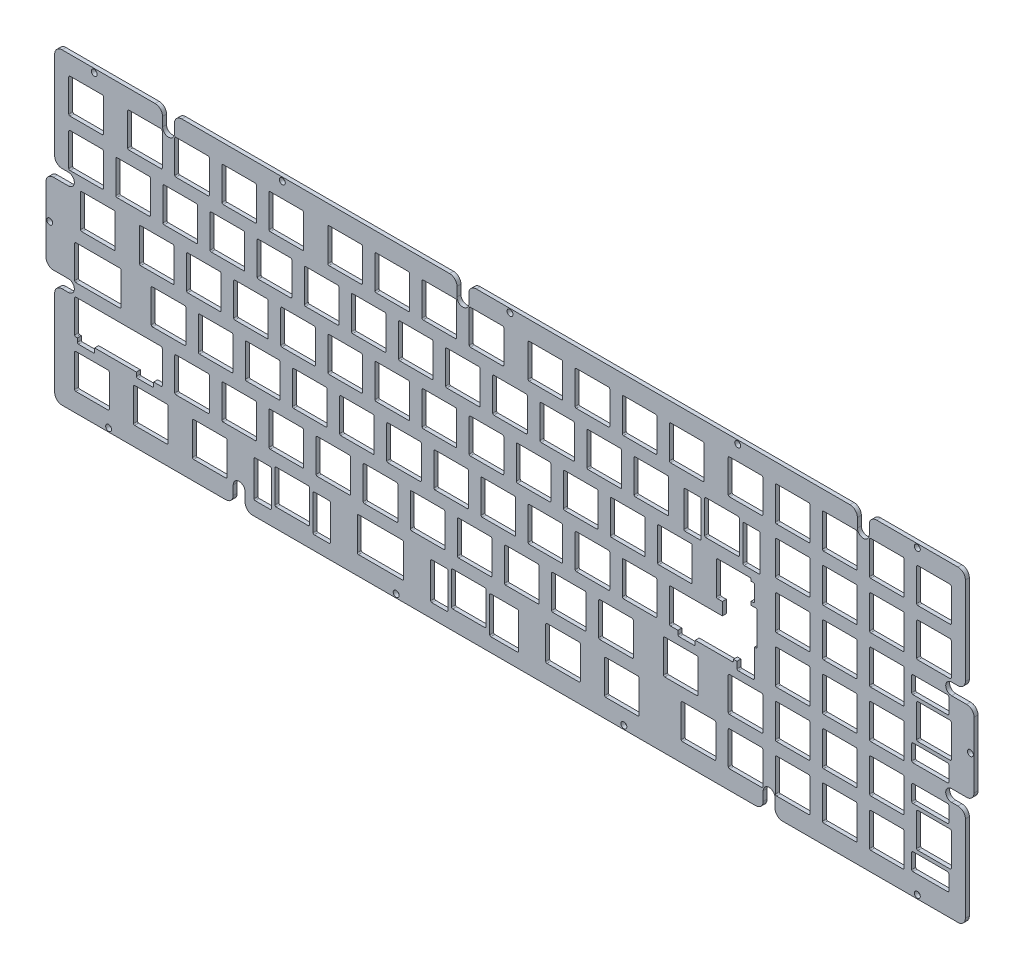
SolidWorks part; units mm, degrees
ref_plane "Front Plane" through (0, 0, 0) normal (0, 0, 1) x (1, 0, 0)
ref_plane "Top Plane" through (0, 0, 0) normal (0, 1, 0) x (1, 0, 0)
ref_plane "Right Plane" through (0, 0, 0) normal (1, 0, 0) x (0, 0, -1)
sketch "Model" plane through (0, 0, 0) normal (0, 0, 1) x (1, 0, 0)
  line L0 (3.025, -2.525) -> (16.025, -2.525)
  line L1 (3.025, -16.525) -> (16.025, -16.525)
  line L2 (2.525, -3.025) -> (2.525, -16.025)
  line L3 (16.525, -3.025) -> (16.525, -16.025)
  line L4 (26.8375, -2.525) -> (39.8375, -2.525)
  line L5 (26.8375, -16.525) -> (39.8375, -16.525)
  line L6 (26.3375, -3.025) -> (26.3375, -16.025)
  line L7 (40.3375, -3.025) -> (40.3375, -16.025)
  line L8 (45.8875, -2.525) -> (58.8875, -2.525)
  line L9 (45.8875, -16.525) -> (58.8875, -16.525)
  line L10 (45.3875, -3.025) -> (45.3875, -16.025)
  line L11 (59.3875, -3.025) -> (59.3875, -16.025)
  line L12 (64.9375, -2.525) -> (77.9375, -2.525)
  line L13 (64.9375, -16.525) -> (77.9375, -16.525)
  line L14 (64.4375, -3.025) -> (64.4375, -16.025)
  line L15 (78.4375, -3.025) -> (78.4375, -16.025)
  line L16 (83.9875, -2.525) -> (96.9875, -2.525)
  line L17 (83.9875, -16.525) -> (96.9875, -16.525)
  line L18 (83.4875, -3.025) -> (83.4875, -16.025)
  line L19 (97.4875, -3.025) -> (97.4875, -16.025)
  line L20 (107.8, -2.525) -> (120.8, -2.525)
  line L21 (107.8, -16.525) -> (120.8, -16.525)
  line L22 (107.3, -3.025) -> (107.3, -16.025)
  line L23 (121.3, -3.025) -> (121.3, -16.025)
  line L24 (126.85, -2.525) -> (139.85, -2.525)
  line L25 (126.85, -16.525) -> (139.85, -16.525)
  line L26 (126.35, -3.025) -> (126.35, -16.025)
  line L27 (140.35, -3.025) -> (140.35, -16.025)
  line L28 (145.9, -2.525) -> (158.9, -2.525)
  line L29 (145.9, -16.525) -> (158.9, -16.525)
  line L30 (145.4, -3.025) -> (145.4, -16.025)
  line L31 (159.4, -3.025) -> (159.4, -16.025)
  line L32 (164.95, -2.525) -> (177.95, -2.525)
  line L33 (164.95, -16.525) -> (177.95, -16.525)
  line L34 (164.45, -3.025) -> (164.45, -16.025)
  line L35 (178.45, -3.025) -> (178.45, -16.025)
  line L36 (188.7625, -2.525) -> (201.7625, -2.525)
  line L37 (188.7625, -16.525) -> (201.7625, -16.525)
  line L38 (188.2625, -3.025) -> (188.2625, -16.025)
  line L39 (202.2625, -3.025) -> (202.2625, -16.025)
  line L40 (207.8125, -2.525) -> (220.8125, -2.525)
  line L41 (207.8125, -16.525) -> (220.8125, -16.525)
  line L42 (207.3125, -3.025) -> (207.3125, -16.025)
  line L43 (221.3125, -3.025) -> (221.3125, -16.025)
  line L44 (226.8625, -2.525) -> (239.8625, -2.525)
  line L45 (226.8625, -16.525) -> (239.8625, -16.525)
  line L46 (226.3625, -3.025) -> (226.3625, -16.025)
  line L47 (240.3625, -3.025) -> (240.3625, -16.025)
  line L48 (245.9125, -2.525) -> (258.9125, -2.525)
  line L49 (245.9125, -16.525) -> (258.9125, -16.525)
  line L50 (245.4125, -3.025) -> (245.4125, -16.025)
  line L51 (259.4125, -3.025) -> (259.4125, -16.025)
  line L52 (269.725, -2.525) -> (282.725, -2.525)
  line L53 (269.725, -16.525) -> (282.725, -16.525)
  line L54 (269.225, -3.025) -> (269.225, -16.025)
  line L55 (283.225, -3.025) -> (283.225, -16.025)
  line L56 (288.775, -2.525) -> (301.775, -2.525)
  line L57 (288.775, -16.525) -> (301.775, -16.525)
  line L58 (288.275, -3.025) -> (288.275, -16.025)
  line L59 (302.275, -3.025) -> (302.275, -16.025)
  line L60 (307.825, -2.525) -> (320.825, -2.525)
  line L61 (307.825, -16.525) -> (320.825, -16.525)
  line L62 (307.325, -3.025) -> (307.325, -16.025)
  line L63 (321.325, -3.025) -> (321.325, -16.025)
  line L64 (326.875, -2.525) -> (339.875, -2.525)
  line L65 (326.875, -16.525) -> (339.875, -16.525)
  line L66 (326.375, -3.025) -> (326.375, -16.025)
  line L67 (340.375, -3.025) -> (340.375, -16.025)
  line L68 (345.925, -2.525) -> (358.925, -2.525)
  line L69 (345.925, -16.525) -> (358.925, -16.525)
  line L70 (345.425, -3.025) -> (345.425, -16.025)
  line L71 (359.425, -3.025) -> (359.425, -16.025)
  line L72 (3.025, -21.575) -> (16.025, -21.575)
  line L73 (3.025, -35.575) -> (16.025, -35.575)
  line L74 (2.525, -22.075) -> (2.525, -35.075)
  line L75 (16.525, -22.075) -> (16.525, -35.075)
  line L76 (22.075, -21.575) -> (35.075, -21.575)
  line L77 (22.075, -35.575) -> (35.075, -35.575)
  line L78 (21.575, -22.075) -> (21.575, -35.075)
  line L79 (35.575, -22.075) -> (35.575, -35.075)
  line L80 (41.125, -21.575) -> (54.125, -21.575)
  line L81 (41.125, -35.575) -> (54.125, -35.575)
  line L82 (40.625, -22.075) -> (40.625, -35.075)
  line L83 (54.625, -22.075) -> (54.625, -35.075)
  line L84 (60.175, -21.575) -> (73.175, -21.575)
  line L85 (60.175, -35.575) -> (73.175, -35.575)
  line L86 (59.675, -22.075) -> (59.675, -35.075)
  line L87 (73.675, -22.075) -> (73.675, -35.075)
  line L88 (79.225, -21.575) -> (92.225, -21.575)
  line L89 (79.225, -35.575) -> (92.225, -35.575)
  line L90 (78.725, -22.075) -> (78.725, -35.075)
  line L91 (92.725, -22.075) -> (92.725, -35.075)
  line L92 (98.275, -21.575) -> (111.275, -21.575)
  line L93 (98.275, -35.575) -> (111.275, -35.575)
  line L94 (97.775, -22.075) -> (97.775, -35.075)
  line L95 (111.775, -22.075) -> (111.775, -35.075)
  line L96 (117.325, -21.575) -> (130.325, -21.575)
  line L97 (117.325, -35.575) -> (130.325, -35.575)
  line L98 (116.825, -22.075) -> (116.825, -35.075)
  line L99 (130.825, -22.075) -> (130.825, -35.075)
  line L100 (136.375, -21.575) -> (149.375, -21.575)
  line L101 (136.375, -35.575) -> (149.375, -35.575)
  line L102 (135.875, -22.075) -> (135.875, -35.075)
  line L103 (149.875, -22.075) -> (149.875, -35.075)
  line L104 (155.425, -21.575) -> (168.425, -21.575)
  line L105 (155.425, -35.575) -> (168.425, -35.575)
  line L106 (154.925, -22.075) -> (154.925, -35.075)
  line L107 (168.925, -22.075) -> (168.925, -35.075)
  line L108 (174.475, -21.575) -> (187.475, -21.575)
  line L109 (174.475, -35.575) -> (187.475, -35.575)
  line L110 (173.975, -22.075) -> (173.975, -35.075)
  line L111 (187.975, -22.075) -> (187.975, -35.075)
  line L112 (193.525, -21.575) -> (206.525, -21.575)
  line L113 (193.525, -35.575) -> (206.525, -35.575)
  line L114 (193.025, -22.075) -> (193.025, -35.075)
  line L115 (207.025, -22.075) -> (207.025, -35.075)
  line L116 (212.575, -21.575) -> (225.575, -21.575)
  line L117 (212.575, -35.575) -> (225.575, -35.575)
  line L118 (212.075, -22.075) -> (212.075, -35.075)
  line L119 (226.075, -22.075) -> (226.075, -35.075)
  line L120 (231.625, -21.575) -> (244.625, -21.575)
  line L121 (231.625, -35.575) -> (244.625, -35.575)
  line L122 (231.125, -22.075) -> (231.125, -35.075)
  line L123 (245.125, -22.075) -> (245.125, -35.075)
  line L124 (260.2, -21.575) -> (273.2, -21.575)
  line L125 (260.2, -35.575) -> (273.2, -35.575)
  line L126 (259.7, -22.075) -> (259.7, -35.075)
  line L127 (273.7, -22.075) -> (273.7, -35.075)
  line L128 (275.638, -22.575) -> (281.638, -22.575)
  line L129 (275.638, -37.575) -> (281.638, -37.575)
  line L130 (275.138, -23.075) -> (275.138, -37.075)
  line L131 (282.138, -23.075) -> (282.138, -37.075)
  line L132 (251.762, -22.575) -> (257.762, -22.575)
  line L133 (251.762, -37.575) -> (257.762, -37.575)
  line L134 (251.262, -23.075) -> (251.262, -37.075)
  line L135 (258.262, -23.075) -> (258.262, -37.075)
  line L136 (288.775, -21.575) -> (301.775, -21.575)
  line L137 (288.775, -35.575) -> (301.775, -35.575)
  line L138 (288.275, -22.075) -> (288.275, -35.075)
  line L139 (302.275, -22.075) -> (302.275, -35.075)
  line L140 (307.825, -21.575) -> (320.825, -21.575)
  line L141 (307.825, -35.575) -> (320.825, -35.575)
  line L142 (307.325, -22.075) -> (307.325, -35.075)
  line L143 (321.325, -22.075) -> (321.325, -35.075)
  line L144 (326.875, -21.575) -> (339.875, -21.575)
  line L145 (326.875, -35.575) -> (339.875, -35.575)
  line L146 (326.375, -22.075) -> (326.375, -35.075)
  line L147 (340.375, -22.075) -> (340.375, -35.075)
  line L148 (345.925, -21.575) -> (358.925, -21.575)
  line L149 (345.925, -35.575) -> (358.925, -35.575)
  line L150 (345.425, -22.075) -> (345.425, -35.075)
  line L151 (359.425, -22.075) -> (359.425, -35.075)
  line L152 (7.7875, -40.625) -> (20.7875, -40.625)
  line L153 (7.7875, -54.625) -> (20.7875, -54.625)
  line L154 (7.2875, -41.125) -> (7.2875, -54.125)
  line L155 (21.2875, -41.125) -> (21.2875, -54.125)
  line L156 (31.6, -40.625) -> (44.6, -40.625)
  line L157 (31.6, -54.625) -> (44.6, -54.625)
  line L158 (31.1, -41.125) -> (31.1, -54.125)
  line L159 (45.1, -41.125) -> (45.1, -54.125)
  line L160 (50.65, -40.625) -> (63.65, -40.625)
  line L161 (50.65, -54.625) -> (63.65, -54.625)
  line L162 (50.15, -41.125) -> (50.15, -54.125)
  line L163 (64.15, -41.125) -> (64.15, -54.125)
  line L164 (69.7, -40.625) -> (82.7, -40.625)
  line L165 (69.7, -54.625) -> (82.7, -54.625)
  line L166 (69.2, -41.125) -> (69.2, -54.125)
  line L167 (83.2, -41.125) -> (83.2, -54.125)
  line L168 (88.75, -40.625) -> (101.75, -40.625)
  line L169 (88.75, -54.625) -> (101.75, -54.625)
  line L170 (88.25, -41.125) -> (88.25, -54.125)
  line L171 (102.25, -41.125) -> (102.25, -54.125)
  line L172 (107.8, -40.625) -> (120.8, -40.625)
  line L173 (107.8, -54.625) -> (120.8, -54.625)
  line L174 (107.3, -41.125) -> (107.3, -54.125)
  line L175 (121.3, -41.125) -> (121.3, -54.125)
  line L176 (126.85, -40.625) -> (139.85, -40.625)
  line L177 (126.85, -54.625) -> (139.85, -54.625)
  line L178 (126.35, -41.125) -> (126.35, -54.125)
  line L179 (140.35, -41.125) -> (140.35, -54.125)
  line L180 (145.9, -40.625) -> (158.9, -40.625)
  line L181 (145.9, -54.625) -> (158.9, -54.625)
  line L182 (145.4, -41.125) -> (145.4, -54.125)
  line L183 (159.4, -41.125) -> (159.4, -54.125)
  line L184 (164.95, -40.625) -> (177.95, -40.625)
  line L185 (164.95, -54.625) -> (177.95, -54.625)
  line L186 (164.45, -41.125) -> (164.45, -54.125)
  line L187 (178.45, -41.125) -> (178.45, -54.125)
  line L188 (184, -40.625) -> (197, -40.625)
  line L189 (184, -54.625) -> (197, -54.625)
  line L190 (183.5, -41.125) -> (183.5, -54.125)
  line L191 (197.5, -41.125) -> (197.5, -54.125)
  line L192 (203.05, -40.625) -> (216.05, -40.625)
  line L193 (203.05, -54.625) -> (216.05, -54.625)
  line L194 (202.55, -41.125) -> (202.55, -54.125)
  line L195 (216.55, -41.125) -> (216.55, -54.125)
  line L196 (222.1, -40.625) -> (235.1, -40.625)
  line L197 (222.1, -54.625) -> (235.1, -54.625)
  line L198 (221.6, -41.125) -> (221.6, -54.125)
  line L199 (235.6, -41.125) -> (235.6, -54.125)
  line L200 (241.15, -40.625) -> (254.15, -40.625)
  line L201 (241.15, -54.625) -> (254.15, -54.625)
  line L202 (240.65, -41.125) -> (240.65, -54.125)
  line L203 (254.65, -41.125) -> (254.65, -54.125)
  line L204 (264.9625, -40.625) -> (277.9625, -40.625)
  line L205 (264.9625, -54.625) -> (277.9625, -54.625)
  line L206 (264.4625, -41.125) -> (264.4625, -54.125)
  line L207 (278.4625, -41.125) -> (278.4625, -54.125)
  line L208 (280.8438, -50.65) -> (280.8438, -63.65)
  line L209 (266.8438, -50.65) -> (266.8438, -63.65)
  line L210 (280.3438, -50.15) -> (267.3438, -50.15)
  line L211 (280.3438, -64.15) -> (267.3438, -64.15)
  line L212 (279.8438, -66.088) -> (279.8438, -72.088)
  line L213 (264.8438, -66.088) -> (264.8438, -72.088)
  line L214 (279.3438, -65.588) -> (265.3438, -65.588)
  line L215 (279.3438, -72.588) -> (265.3438, -72.588)
  line L216 (279.8438, -42.212) -> (279.8438, -48.212)
  line L217 (264.8438, -42.212) -> (264.8438, -48.212)
  line L218 (279.3438, -41.712) -> (265.3438, -41.712)
  line L219 (279.3438, -48.712) -> (265.3438, -48.712)
  line L220 (288.775, -40.625) -> (301.775, -40.625)
  line L221 (288.775, -54.625) -> (301.775, -54.625)
  line L222 (288.275, -41.125) -> (288.275, -54.125)
  line L223 (302.275, -41.125) -> (302.275, -54.125)
  line L224 (307.825, -40.625) -> (320.825, -40.625)
  line L225 (307.825, -54.625) -> (320.825, -54.625)
  line L226 (307.325, -41.125) -> (307.325, -54.125)
  line L227 (321.325, -41.125) -> (321.325, -54.125)
  line L228 (326.875, -40.625) -> (339.875, -40.625)
  line L229 (326.875, -54.625) -> (339.875, -54.625)
  line L230 (326.375, -41.125) -> (326.375, -54.125)
  line L231 (340.375, -41.125) -> (340.375, -54.125)
  line L232 (359.425, -50.65) -> (359.425, -63.65)
  line L233 (345.425, -50.65) -> (345.425, -63.65)
  line L234 (358.925, -50.15) -> (345.925, -50.15)
  line L235 (358.925, -64.15) -> (345.925, -64.15)
  line L236 (358.425, -66.088) -> (358.425, -72.088)
  line L237 (343.425, -66.088) -> (343.425, -72.088)
  line L238 (357.925, -65.588) -> (343.925, -65.588)
  line L239 (357.925, -72.588) -> (343.925, -72.588)
  line L240 (358.425, -42.212) -> (358.425, -48.212)
  line L241 (343.425, -42.212) -> (343.425, -48.212)
  line L242 (357.925, -41.712) -> (343.925, -41.712)
  line L243 (357.925, -48.712) -> (343.925, -48.712)
  line L244 (10.1687, -59.675) -> (23.1687, -59.675)
  line L245 (10.1687, -73.675) -> (23.1687, -73.675)
  line L246 (9.6688, -60.175) -> (9.6688, -73.175)
  line L247 (23.6687, -60.175) -> (23.6687, -73.175)
  line L248 (5.4063, -59.675) -> (18.4062, -59.675)
  line L249 (5.4063, -73.675) -> (18.4062, -73.675)
  line L250 (4.9062, -60.175) -> (4.9062, -73.175)
  line L251 (18.9062, -60.175) -> (18.9062, -73.175)
  line L252 (36.3625, -59.675) -> (49.3625, -59.675)
  line L253 (36.3625, -73.675) -> (49.3625, -73.675)
  line L254 (35.8625, -60.175) -> (35.8625, -73.175)
  line L255 (49.8625, -60.175) -> (49.8625, -73.175)
  line L256 (55.4125, -59.675) -> (68.4125, -59.675)
  line L257 (55.4125, -73.675) -> (68.4125, -73.675)
  line L258 (54.9125, -60.175) -> (54.9125, -73.175)
  line L259 (68.9125, -60.175) -> (68.9125, -73.175)
  line L260 (74.4625, -59.675) -> (87.4625, -59.675)
  line L261 (74.4625, -73.675) -> (87.4625, -73.675)
  line L262 (73.9625, -60.175) -> (73.9625, -73.175)
  line L263 (87.9625, -60.175) -> (87.9625, -73.175)
  line L264 (93.5125, -59.675) -> (106.5125, -59.675)
  line L265 (93.5125, -73.675) -> (106.5125, -73.675)
  line L266 (93.0125, -60.175) -> (93.0125, -73.175)
  line L267 (107.0125, -60.175) -> (107.0125, -73.175)
  line L268 (112.5625, -59.675) -> (125.5625, -59.675)
  line L269 (112.5625, -73.675) -> (125.5625, -73.675)
  line L270 (112.0625, -60.175) -> (112.0625, -73.175)
  line L271 (126.0625, -60.175) -> (126.0625, -73.175)
  line L272 (131.6125, -59.675) -> (144.6125, -59.675)
  line L273 (131.6125, -73.675) -> (144.6125, -73.675)
  line L274 (131.1125, -60.175) -> (131.1125, -73.175)
  line L275 (145.1125, -60.175) -> (145.1125, -73.175)
  line L276 (150.6625, -59.675) -> (163.6625, -59.675)
  line L277 (150.6625, -73.675) -> (163.6625, -73.675)
  line L278 (150.1625, -60.175) -> (150.1625, -73.175)
  line L279 (164.1625, -60.175) -> (164.1625, -73.175)
  line L280 (169.7125, -59.675) -> (182.7125, -59.675)
  line L281 (169.7125, -73.675) -> (182.7125, -73.675)
  line L282 (169.2125, -60.175) -> (169.2125, -73.175)
  line L283 (183.2125, -60.175) -> (183.2125, -73.175)
  line L284 (188.7625, -59.675) -> (201.7625, -59.675)
  line L285 (188.7625, -73.675) -> (201.7625, -73.675)
  line L286 (188.2625, -60.175) -> (188.2625, -73.175)
  line L287 (202.2625, -60.175) -> (202.2625, -73.175)
  line L288 (207.8125, -59.675) -> (220.8125, -59.675)
  line L289 (207.8125, -73.675) -> (220.8125, -73.675)
  line L290 (207.3125, -60.175) -> (207.3125, -73.175)
  line L291 (221.3125, -60.175) -> (221.3125, -73.175)
  line L292 (226.8625, -59.675) -> (239.8625, -59.675)
  line L293 (226.8625, -73.675) -> (239.8625, -73.675)
  line L294 (226.3625, -60.175) -> (226.3625, -73.175)
  line L295 (240.3625, -60.175) -> (240.3625, -73.175)
  line L296 (245.9125, -59.675) -> (258.9125, -59.675)
  line L297 (245.9125, -73.675) -> (258.9125, -73.675)
  line L298 (245.4125, -60.175) -> (245.4125, -73.175)
  line L299 (259.4125, -60.175) -> (259.4125, -73.175)
  line L300 (257.8188, -59.675) -> (270.8188, -59.675)
  line L301 (257.8188, -73.675) -> (270.8188, -73.675)
  line L302 (257.3188, -60.175) -> (257.3188, -73.175)
  line L303 (271.3188, -60.175) -> (271.3188, -73.175)
  line L304 (273.2568, -60.675) -> (279.2568, -60.675)
  line L305 (273.2568, -75.675) -> (279.2568, -75.675)
  line L306 (272.7568, -61.175) -> (272.7568, -75.175)
  line L307 (279.7568, -61.175) -> (279.7568, -75.175)
  line L308 (249.3808, -60.675) -> (255.3807, -60.675)
  line L309 (249.3808, -75.675) -> (255.3807, -75.675)
  line L310 (248.8808, -61.175) -> (248.8808, -75.175)
  line L311 (255.8807, -61.175) -> (255.8807, -75.175)
  line L312 (288.775, -59.675) -> (301.775, -59.675)
  line L313 (288.775, -73.675) -> (301.775, -73.675)
  line L314 (288.275, -60.175) -> (288.275, -73.175)
  line L315 (302.275, -60.175) -> (302.275, -73.175)
  line L316 (307.825, -59.675) -> (320.825, -59.675)
  line L317 (307.825, -73.675) -> (320.825, -73.675)
  line L318 (307.325, -60.175) -> (307.325, -73.175)
  line L319 (321.325, -60.175) -> (321.325, -73.175)
  line L320 (326.875, -59.675) -> (339.875, -59.675)
  line L321 (326.875, -73.675) -> (339.875, -73.675)
  line L322 (326.375, -60.175) -> (326.375, -73.175)
  line L323 (340.375, -60.175) -> (340.375, -73.175)
  line L324 (5.4063, -78.725) -> (18.4062, -78.725)
  line L325 (5.4063, -92.725) -> (18.4062, -92.725)
  line L326 (4.9062, -79.225) -> (4.9062, -92.225)
  line L327 (18.9062, -79.225) -> (18.9062, -92.225)
  line L328 (14.9313, -78.725) -> (27.9312, -78.725)
  line L329 (14.9313, -92.725) -> (27.9312, -92.725)
  line L330 (14.4313, -79.225) -> (14.4313, -92.225)
  line L331 (28.4312, -79.225) -> (28.4312, -92.225)
  line L332 (30.3693, -79.725) -> (36.3693, -79.725)
  line L333 (30.3693, -94.725) -> (36.3693, -94.725)
  line L334 (29.8693, -80.225) -> (29.8693, -94.225)
  line L335 (36.8693, -80.225) -> (36.8693, -94.225)
  line L336 (6.4932, -79.725) -> (12.4932, -79.725)
  line L337 (6.4932, -94.725) -> (12.4932, -94.725)
  line L338 (5.9932, -80.225) -> (5.9932, -94.225)
  line L339 (12.9932, -80.225) -> (12.9932, -94.225)
  line L340 (26.8375, -78.725) -> (39.8375, -78.725)
  line L341 (26.8375, -92.725) -> (39.8375, -92.725)
  line L342 (26.3375, -79.225) -> (26.3375, -92.225)
  line L343 (40.3375, -79.225) -> (40.3375, -92.225)
  line L344 (45.8875, -78.725) -> (58.8875, -78.725)
  line L345 (45.8875, -92.725) -> (58.8875, -92.725)
  line L346 (45.3875, -79.225) -> (45.3875, -92.225)
  line L347 (59.3875, -79.225) -> (59.3875, -92.225)
  line L348 (64.9375, -78.725) -> (77.9375, -78.725)
  line L349 (64.9375, -92.725) -> (77.9375, -92.725)
  line L350 (64.4375, -79.225) -> (64.4375, -92.225)
  line L351 (78.4375, -79.225) -> (78.4375, -92.225)
  line L352 (83.9875, -78.725) -> (96.9875, -78.725)
  line L353 (83.9875, -92.725) -> (96.9875, -92.725)
  line L354 (83.4875, -79.225) -> (83.4875, -92.225)
  line L355 (97.4875, -79.225) -> (97.4875, -92.225)
  line L356 (103.0375, -78.725) -> (116.0375, -78.725)
  line L357 (103.0375, -92.725) -> (116.0375, -92.725)
  line L358 (102.5375, -79.225) -> (102.5375, -92.225)
  line L359 (116.5375, -79.225) -> (116.5375, -92.225)
  line L360 (122.0875, -78.725) -> (135.0875, -78.725)
  line L361 (122.0875, -92.725) -> (135.0875, -92.725)
  line L362 (121.5875, -79.225) -> (121.5875, -92.225)
  line L363 (135.5875, -79.225) -> (135.5875, -92.225)
  line L364 (141.1375, -78.725) -> (154.1375, -78.725)
  line L365 (141.1375, -92.725) -> (154.1375, -92.725)
  line L366 (140.6375, -79.225) -> (140.6375, -92.225)
  line L367 (154.6375, -79.225) -> (154.6375, -92.225)
  line L368 (160.1875, -78.725) -> (173.1875, -78.725)
  line L369 (160.1875, -92.725) -> (173.1875, -92.725)
  line L370 (159.6875, -79.225) -> (159.6875, -92.225)
  line L371 (173.6875, -79.225) -> (173.6875, -92.225)
  line L372 (179.2375, -78.725) -> (192.2375, -78.725)
  line L373 (179.2375, -92.725) -> (192.2375, -92.725)
  line L374 (178.7375, -79.225) -> (178.7375, -92.225)
  line L375 (192.7375, -79.225) -> (192.7375, -92.225)
  line L376 (198.2875, -78.725) -> (211.2875, -78.725)
  line L377 (198.2875, -92.725) -> (211.2875, -92.725)
  line L378 (197.7875, -79.225) -> (197.7875, -92.225)
  line L379 (211.7875, -79.225) -> (211.7875, -92.225)
  line L380 (217.3375, -78.725) -> (230.3375, -78.725)
  line L381 (217.3375, -92.725) -> (230.3375, -92.725)
  line L382 (216.8375, -79.225) -> (216.8375, -92.225)
  line L383 (230.8375, -79.225) -> (230.8375, -92.225)
  line L384 (243.5312, -78.725) -> (256.5312, -78.725)
  line L385 (243.5312, -92.725) -> (256.5312, -92.725)
  line L386 (243.0312, -79.225) -> (243.0312, -92.225)
  line L387 (257.0312, -79.225) -> (257.0312, -92.225)
  line L388 (269.725, -78.725) -> (282.725, -78.725)
  line L389 (269.725, -92.725) -> (282.725, -92.725)
  line L390 (269.225, -79.225) -> (269.225, -92.225)
  line L391 (283.225, -79.225) -> (283.225, -92.225)
  line L392 (288.775, -78.725) -> (301.775, -78.725)
  line L393 (288.775, -92.725) -> (301.775, -92.725)
  line L394 (288.275, -79.225) -> (288.275, -92.225)
  line L395 (302.275, -79.225) -> (302.275, -92.225)
  line L396 (307.825, -78.725) -> (320.825, -78.725)
  line L397 (307.825, -92.725) -> (320.825, -92.725)
  line L398 (307.325, -79.225) -> (307.325, -92.225)
  line L399 (321.325, -79.225) -> (321.325, -92.225)
  line L400 (326.875, -78.725) -> (339.875, -78.725)
  line L401 (326.875, -92.725) -> (339.875, -92.725)
  line L402 (326.375, -79.225) -> (326.375, -92.225)
  line L403 (340.375, -79.225) -> (340.375, -92.225)
  line L404 (359.425, -88.75) -> (359.425, -101.75)
  line L405 (345.425, -88.75) -> (345.425, -101.75)
  line L406 (358.925, -88.25) -> (345.925, -88.25)
  line L407 (358.925, -102.25) -> (345.925, -102.25)
  line L408 (358.425, -104.188) -> (358.425, -110.188)
  line L409 (343.425, -104.188) -> (343.425, -110.188)
  line L410 (357.925, -103.688) -> (343.925, -103.688)
  line L411 (357.925, -110.688) -> (343.925, -110.688)
  line L412 (358.425, -80.312) -> (358.425, -86.312)
  line L413 (343.425, -80.312) -> (343.425, -86.312)
  line L414 (357.925, -79.812) -> (343.925, -79.812)
  line L415 (357.925, -86.812) -> (343.925, -86.812)
  line L416 (5.4063, -97.775) -> (18.4062, -97.775)
  line L417 (5.4063, -111.775) -> (18.4062, -111.775)
  line L418 (4.9062, -98.275) -> (4.9062, -111.275)
  line L419 (18.9062, -98.275) -> (18.9062, -111.275)
  line L420 (29.2188, -97.775) -> (42.2188, -97.775)
  line L421 (29.2188, -111.775) -> (42.2188, -111.775)
  line L422 (28.7188, -98.275) -> (28.7188, -111.275)
  line L423 (42.7188, -98.275) -> (42.7188, -111.275)
  line L424 (53.0312, -97.775) -> (66.0312, -97.775)
  line L425 (53.0312, -111.775) -> (66.0312, -111.775)
  line L426 (52.5312, -98.275) -> (52.5312, -111.275)
  line L427 (66.5312, -98.275) -> (66.5312, -111.275)
  line L428 (124.4688, -97.775) -> (137.4688, -97.775)
  line L429 (124.4688, -111.775) -> (137.4688, -111.775)
  line L430 (123.9688, -98.275) -> (123.9688, -111.275)
  line L431 (137.9688, -98.275) -> (137.9688, -111.275)
  line L432 (177.9688, -98.775) -> (183.9688, -98.775)
  line L433 (177.9688, -113.775) -> (183.9688, -113.775)
  line L434 (177.4688, -99.275) -> (177.4688, -113.275)
  line L435 (184.4688, -99.275) -> (184.4688, -113.275)
  line L436 (77.9688, -98.775) -> (83.9688, -98.775)
  line L437 (77.9688, -113.775) -> (83.9688, -113.775)
  line L438 (77.4688, -99.275) -> (77.4688, -113.275)
  line L439 (84.4688, -99.275) -> (84.4688, -113.275)
  line L440 (86.3688, -97.775) -> (99.3688, -97.775)
  line L441 (86.3688, -111.775) -> (99.3688, -111.775)
  line L442 (85.8688, -98.275) -> (85.8688, -111.275)
  line L443 (99.8688, -98.275) -> (99.8688, -111.275)
  line L444 (101.8068, -98.775) -> (107.8067, -98.775)
  line L445 (101.8068, -113.775) -> (107.8067, -113.775)
  line L446 (101.3067, -99.275) -> (101.3067, -113.275)
  line L447 (108.3067, -99.275) -> (108.3067, -113.275)
  line L448 (77.9308, -98.775) -> (83.9308, -98.775)
  line L449 (77.9308, -113.775) -> (83.9308, -113.775)
  line L450 (77.4308, -99.275) -> (77.4308, -113.275)
  line L451 (84.4308, -99.275) -> (84.4308, -113.275)
  line L452 (119.7062, -97.775) -> (132.7063, -97.775)
  line L453 (119.7062, -111.775) -> (132.7063, -111.775)
  line L454 (119.2062, -98.275) -> (119.2062, -111.275)
  line L455 (133.2063, -98.275) -> (133.2063, -111.275)
  line L456 (157.8063, -97.775) -> (170.8063, -97.775)
  line L457 (157.8063, -111.775) -> (170.8063, -111.775)
  line L458 (157.3063, -98.275) -> (157.3063, -111.275)
  line L459 (171.3063, -98.275) -> (171.3063, -111.275)
  line L460 (173.2442, -98.775) -> (179.2442, -98.775)
  line L461 (173.2442, -113.775) -> (179.2442, -113.775)
  line L462 (172.7442, -99.275) -> (172.7442, -113.275)
  line L463 (179.7442, -99.275) -> (179.7442, -113.275)
  line L464 (149.3682, -98.775) -> (155.3682, -98.775)
  line L465 (149.3682, -113.775) -> (155.3682, -113.775)
  line L466 (148.8682, -99.275) -> (148.8682, -113.275)
  line L467 (155.8682, -99.275) -> (155.8682, -113.275)
  line L468 (195.9062, -97.775) -> (208.9063, -97.775)
  line L469 (195.9062, -111.775) -> (208.9063, -111.775)
  line L470 (195.4062, -98.275) -> (195.4062, -111.275)
  line L471 (209.4063, -98.275) -> (209.4063, -111.275)
  line L472 (219.7188, -97.775) -> (232.7188, -97.775)
  line L473 (219.7188, -111.775) -> (232.7188, -111.775)
  line L474 (219.2188, -98.275) -> (219.2188, -111.275)
  line L475 (233.2188, -98.275) -> (233.2188, -111.275)
  line L476 (250.675, -97.775) -> (263.675, -97.775)
  line L477 (250.675, -111.775) -> (263.675, -111.775)
  line L478 (250.175, -98.275) -> (250.175, -111.275)
  line L479 (264.175, -98.275) -> (264.175, -111.275)
  line L480 (269.725, -97.775) -> (282.725, -97.775)
  line L481 (269.725, -111.775) -> (282.725, -111.775)
  line L482 (269.225, -98.275) -> (269.225, -111.275)
  line L483 (283.225, -98.275) -> (283.225, -111.275)
  line L484 (288.775, -97.775) -> (301.775, -97.775)
  line L485 (288.775, -111.775) -> (301.775, -111.775)
  line L486 (288.275, -98.275) -> (288.275, -111.275)
  line L487 (302.275, -98.275) -> (302.275, -111.275)
  line L488 (307.825, -97.775) -> (320.825, -97.775)
  line L489 (307.825, -111.775) -> (320.825, -111.775)
  line L490 (307.325, -98.275) -> (307.325, -111.275)
  line L491 (321.325, -98.275) -> (321.325, -111.275)
  line L492 (326.875, -97.775) -> (339.875, -97.775)
  line L493 (326.875, -111.775) -> (339.875, -111.775)
  line L494 (326.375, -98.275) -> (326.375, -111.275)
  line L495 (340.375, -98.275) -> (340.375, -111.275)
  line L496 (0, 0) -> (361.95, 0)
  line L497 (0, -114.3) -> (361.95, -114.3)
  line L498 (0, 0) -> (0, -114.3)
  line L499 (361.95, 0) -> (361.95, -114.3)
  arc A0 (3.025, -2.525) -> (2.525, -3.025) centre (3.025, -3.025) ccw
  arc A1 (16.525, -3.025) -> (16.025, -2.525) centre (16.025, -3.025) ccw
  arc A2 (2.525, -16.025) -> (3.025, -16.525) centre (3.025, -16.025) ccw
  arc A3 (16.025, -16.525) -> (16.525, -16.025) centre (16.025, -16.025) ccw
  arc A4 (26.8375, -2.525) -> (26.3375, -3.025) centre (26.8375, -3.025) ccw
  arc A5 (40.3375, -3.025) -> (39.8375, -2.525) centre (39.8375, -3.025) ccw
  arc A6 (26.3375, -16.025) -> (26.8375, -16.525) centre (26.8375, -16.025) ccw
  arc A7 (39.8375, -16.525) -> (40.3375, -16.025) centre (39.8375, -16.025) ccw
  arc A8 (45.8875, -2.525) -> (45.3875, -3.025) centre (45.8875, -3.025) ccw
  arc A9 (59.3875, -3.025) -> (58.8875, -2.525) centre (58.8875, -3.025) ccw
  arc A10 (45.3875, -16.025) -> (45.8875, -16.525) centre (45.8875, -16.025) ccw
  arc A11 (58.8875, -16.525) -> (59.3875, -16.025) centre (58.8875, -16.025) ccw
  arc A12 (64.9375, -2.525) -> (64.4375, -3.025) centre (64.9375, -3.025) ccw
  arc A13 (78.4375, -3.025) -> (77.9375, -2.525) centre (77.9375, -3.025) ccw
  arc A14 (64.4375, -16.025) -> (64.9375, -16.525) centre (64.9375, -16.025) ccw
  arc A15 (77.9375, -16.525) -> (78.4375, -16.025) centre (77.9375, -16.025) ccw
  arc A16 (83.9875, -2.525) -> (83.4875, -3.025) centre (83.9875, -3.025) ccw
  arc A17 (97.4875, -3.025) -> (96.9875, -2.525) centre (96.9875, -3.025) ccw
  arc A18 (83.4875, -16.025) -> (83.9875, -16.525) centre (83.9875, -16.025) ccw
  arc A19 (96.9875, -16.525) -> (97.4875, -16.025) centre (96.9875, -16.025) ccw
  arc A20 (107.8, -2.525) -> (107.3, -3.025) centre (107.8, -3.025) ccw
  arc A21 (121.3, -3.025) -> (120.8, -2.525) centre (120.8, -3.025) ccw
  arc A22 (107.3, -16.025) -> (107.8, -16.525) centre (107.8, -16.025) ccw
  arc A23 (120.8, -16.525) -> (121.3, -16.025) centre (120.8, -16.025) ccw
  arc A24 (126.85, -2.525) -> (126.35, -3.025) centre (126.85, -3.025) ccw
  arc A25 (140.35, -3.025) -> (139.85, -2.525) centre (139.85, -3.025) ccw
  arc A26 (126.35, -16.025) -> (126.85, -16.525) centre (126.85, -16.025) ccw
  arc A27 (139.85, -16.525) -> (140.35, -16.025) centre (139.85, -16.025) ccw
  arc A28 (145.9, -2.525) -> (145.4, -3.025) centre (145.9, -3.025) ccw
  arc A29 (159.4, -3.025) -> (158.9, -2.525) centre (158.9, -3.025) ccw
  arc A30 (145.4, -16.025) -> (145.9, -16.525) centre (145.9, -16.025) ccw
  arc A31 (158.9, -16.525) -> (159.4, -16.025) centre (158.9, -16.025) ccw
  arc A32 (164.95, -2.525) -> (164.45, -3.025) centre (164.95, -3.025) ccw
  arc A33 (178.45, -3.025) -> (177.95, -2.525) centre (177.95, -3.025) ccw
  arc A34 (164.45, -16.025) -> (164.95, -16.525) centre (164.95, -16.025) ccw
  arc A35 (177.95, -16.525) -> (178.45, -16.025) centre (177.95, -16.025) ccw
  arc A36 (188.7625, -2.525) -> (188.2625, -3.025) centre (188.7625, -3.025) ccw
  arc A37 (202.2625, -3.025) -> (201.7625, -2.525) centre (201.7625, -3.025) ccw
  arc A38 (188.2625, -16.025) -> (188.7625, -16.525) centre (188.7625, -16.025) ccw
  arc A39 (201.7625, -16.525) -> (202.2625, -16.025) centre (201.7625, -16.025) ccw
  arc A40 (207.8125, -2.525) -> (207.3125, -3.025) centre (207.8125, -3.025) ccw
  arc A41 (221.3125, -3.025) -> (220.8125, -2.525) centre (220.8125, -3.025) ccw
  arc A42 (207.3125, -16.025) -> (207.8125, -16.525) centre (207.8125, -16.025) ccw
  arc A43 (220.8125, -16.525) -> (221.3125, -16.025) centre (220.8125, -16.025) ccw
  arc A44 (226.8625, -2.525) -> (226.3625, -3.025) centre (226.8625, -3.025) ccw
  arc A45 (240.3625, -3.025) -> (239.8625, -2.525) centre (239.8625, -3.025) ccw
  arc A46 (226.3625, -16.025) -> (226.8625, -16.525) centre (226.8625, -16.025) ccw
  arc A47 (239.8625, -16.525) -> (240.3625, -16.025) centre (239.8625, -16.025) ccw
  arc A48 (245.9125, -2.525) -> (245.4125, -3.025) centre (245.9125, -3.025) ccw
  arc A49 (259.4125, -3.025) -> (258.9125, -2.525) centre (258.9125, -3.025) ccw
  arc A50 (245.4125, -16.025) -> (245.9125, -16.525) centre (245.9125, -16.025) ccw
  arc A51 (258.9125, -16.525) -> (259.4125, -16.025) centre (258.9125, -16.025) ccw
  arc A52 (269.725, -2.525) -> (269.225, -3.025) centre (269.725, -3.025) ccw
  arc A53 (283.225, -3.025) -> (282.725, -2.525) centre (282.725, -3.025) ccw
  arc A54 (269.225, -16.025) -> (269.725, -16.525) centre (269.725, -16.025) ccw
  arc A55 (282.725, -16.525) -> (283.225, -16.025) centre (282.725, -16.025) ccw
  arc A56 (288.775, -2.525) -> (288.275, -3.025) centre (288.775, -3.025) ccw
  arc A57 (302.275, -3.025) -> (301.775, -2.525) centre (301.775, -3.025) ccw
  arc A58 (288.275, -16.025) -> (288.775, -16.525) centre (288.775, -16.025) ccw
  arc A59 (301.775, -16.525) -> (302.275, -16.025) centre (301.775, -16.025) ccw
  arc A60 (307.825, -2.525) -> (307.325, -3.025) centre (307.825, -3.025) ccw
  arc A61 (321.325, -3.025) -> (320.825, -2.525) centre (320.825, -3.025) ccw
  arc A62 (307.325, -16.025) -> (307.825, -16.525) centre (307.825, -16.025) ccw
  arc A63 (320.825, -16.525) -> (321.325, -16.025) centre (320.825, -16.025) ccw
  arc A64 (326.875, -2.525) -> (326.375, -3.025) centre (326.875, -3.025) ccw
  arc A65 (340.375, -3.025) -> (339.875, -2.525) centre (339.875, -3.025) ccw
  arc A66 (326.375, -16.025) -> (326.875, -16.525) centre (326.875, -16.025) ccw
  arc A67 (339.875, -16.525) -> (340.375, -16.025) centre (339.875, -16.025) ccw
  arc A68 (345.925, -2.525) -> (345.425, -3.025) centre (345.925, -3.025) ccw
  arc A69 (359.425, -3.025) -> (358.925, -2.525) centre (358.925, -3.025) ccw
  arc A70 (345.425, -16.025) -> (345.925, -16.525) centre (345.925, -16.025) ccw
  arc A71 (358.925, -16.525) -> (359.425, -16.025) centre (358.925, -16.025) ccw
  arc A72 (3.025, -21.575) -> (2.525, -22.075) centre (3.025, -22.075) ccw
  arc A73 (16.525, -22.075) -> (16.025, -21.575) centre (16.025, -22.075) ccw
  arc A74 (2.525, -35.075) -> (3.025, -35.575) centre (3.025, -35.075) ccw
  arc A75 (16.025, -35.575) -> (16.525, -35.075) centre (16.025, -35.075) ccw
  arc A76 (22.075, -21.575) -> (21.575, -22.075) centre (22.075, -22.075) ccw
  arc A77 (35.575, -22.075) -> (35.075, -21.575) centre (35.075, -22.075) ccw
  arc A78 (21.575, -35.075) -> (22.075, -35.575) centre (22.075, -35.075) ccw
  arc A79 (35.075, -35.575) -> (35.575, -35.075) centre (35.075, -35.075) ccw
  arc A80 (41.125, -21.575) -> (40.625, -22.075) centre (41.125, -22.075) ccw
  arc A81 (54.625, -22.075) -> (54.125, -21.575) centre (54.125, -22.075) ccw
  arc A82 (40.625, -35.075) -> (41.125, -35.575) centre (41.125, -35.075) ccw
  arc A83 (54.125, -35.575) -> (54.625, -35.075) centre (54.125, -35.075) ccw
  arc A84 (60.175, -21.575) -> (59.675, -22.075) centre (60.175, -22.075) ccw
  arc A85 (73.675, -22.075) -> (73.175, -21.575) centre (73.175, -22.075) ccw
  arc A86 (59.675, -35.075) -> (60.175, -35.575) centre (60.175, -35.075) ccw
  arc A87 (73.175, -35.575) -> (73.675, -35.075) centre (73.175, -35.075) ccw
  arc A88 (79.225, -21.575) -> (78.725, -22.075) centre (79.225, -22.075) ccw
  arc A89 (92.725, -22.075) -> (92.225, -21.575) centre (92.225, -22.075) ccw
  arc A90 (78.725, -35.075) -> (79.225, -35.575) centre (79.225, -35.075) ccw
  arc A91 (92.225, -35.575) -> (92.725, -35.075) centre (92.225, -35.075) ccw
  arc A92 (98.275, -21.575) -> (97.775, -22.075) centre (98.275, -22.075) ccw
  arc A93 (111.775, -22.075) -> (111.275, -21.575) centre (111.275, -22.075) ccw
  arc A94 (97.775, -35.075) -> (98.275, -35.575) centre (98.275, -35.075) ccw
  arc A95 (111.275, -35.575) -> (111.775, -35.075) centre (111.275, -35.075) ccw
  arc A96 (117.325, -21.575) -> (116.825, -22.075) centre (117.325, -22.075) ccw
  arc A97 (130.825, -22.075) -> (130.325, -21.575) centre (130.325, -22.075) ccw
  arc A98 (116.825, -35.075) -> (117.325, -35.575) centre (117.325, -35.075) ccw
  arc A99 (130.325, -35.575) -> (130.825, -35.075) centre (130.325, -35.075) ccw
  arc A100 (136.375, -21.575) -> (135.875, -22.075) centre (136.375, -22.075) ccw
  arc A101 (149.875, -22.075) -> (149.375, -21.575) centre (149.375, -22.075) ccw
  arc A102 (135.875, -35.075) -> (136.375, -35.575) centre (136.375, -35.075) ccw
  arc A103 (149.375, -35.575) -> (149.875, -35.075) centre (149.375, -35.075) ccw
  arc A104 (155.425, -21.575) -> (154.925, -22.075) centre (155.425, -22.075) ccw
  arc A105 (168.925, -22.075) -> (168.425, -21.575) centre (168.425, -22.075) ccw
  arc A106 (154.925, -35.075) -> (155.425, -35.575) centre (155.425, -35.075) ccw
  arc A107 (168.425, -35.575) -> (168.925, -35.075) centre (168.425, -35.075) ccw
  arc A108 (174.475, -21.575) -> (173.975, -22.075) centre (174.475, -22.075) ccw
  arc A109 (187.975, -22.075) -> (187.475, -21.575) centre (187.475, -22.075) ccw
  arc A110 (173.975, -35.075) -> (174.475, -35.575) centre (174.475, -35.075) ccw
  arc A111 (187.475, -35.575) -> (187.975, -35.075) centre (187.475, -35.075) ccw
  arc A112 (193.525, -21.575) -> (193.025, -22.075) centre (193.525, -22.075) ccw
  arc A113 (207.025, -22.075) -> (206.525, -21.575) centre (206.525, -22.075) ccw
  arc A114 (193.025, -35.075) -> (193.525, -35.575) centre (193.525, -35.075) ccw
  arc A115 (206.525, -35.575) -> (207.025, -35.075) centre (206.525, -35.075) ccw
  arc A116 (212.575, -21.575) -> (212.075, -22.075) centre (212.575, -22.075) ccw
  arc A117 (226.075, -22.075) -> (225.575, -21.575) centre (225.575, -22.075) ccw
  arc A118 (212.075, -35.075) -> (212.575, -35.575) centre (212.575, -35.075) ccw
  arc A119 (225.575, -35.575) -> (226.075, -35.075) centre (225.575, -35.075) ccw
  arc A120 (231.625, -21.575) -> (231.125, -22.075) centre (231.625, -22.075) ccw
  arc A121 (245.125, -22.075) -> (244.625, -21.575) centre (244.625, -22.075) ccw
  arc A122 (231.125, -35.075) -> (231.625, -35.575) centre (231.625, -35.075) ccw
  arc A123 (244.625, -35.575) -> (245.125, -35.075) centre (244.625, -35.075) ccw
  arc A124 (260.2, -21.575) -> (259.7, -22.075) centre (260.2, -22.075) ccw
  arc A125 (273.7, -22.075) -> (273.2, -21.575) centre (273.2, -22.075) ccw
  arc A126 (259.7, -35.075) -> (260.2, -35.575) centre (260.2, -35.075) ccw
  arc A127 (273.2, -35.575) -> (273.7, -35.075) centre (273.2, -35.075) ccw
  arc A128 (275.638, -22.575) -> (275.138, -23.075) centre (275.638, -23.075) ccw
  arc A129 (282.138, -23.075) -> (281.638, -22.575) centre (281.638, -23.075) ccw
  arc A130 (275.138, -37.075) -> (275.638, -37.575) centre (275.638, -37.075) ccw
  arc A131 (281.638, -37.575) -> (282.138, -37.075) centre (281.638, -37.075) ccw
  arc A132 (251.762, -22.575) -> (251.262, -23.075) centre (251.762, -23.075) ccw
  arc A133 (258.262, -23.075) -> (257.762, -22.575) centre (257.762, -23.075) ccw
  arc A134 (251.262, -37.075) -> (251.762, -37.575) centre (251.762, -37.075) ccw
  arc A135 (257.762, -37.575) -> (258.262, -37.075) centre (257.762, -37.075) ccw
  arc A136 (288.775, -21.575) -> (288.275, -22.075) centre (288.775, -22.075) ccw
  arc A137 (302.275, -22.075) -> (301.775, -21.575) centre (301.775, -22.075) ccw
  arc A138 (288.275, -35.075) -> (288.775, -35.575) centre (288.775, -35.075) ccw
  arc A139 (301.775, -35.575) -> (302.275, -35.075) centre (301.775, -35.075) ccw
  arc A140 (307.825, -21.575) -> (307.325, -22.075) centre (307.825, -22.075) ccw
  arc A141 (321.325, -22.075) -> (320.825, -21.575) centre (320.825, -22.075) ccw
  arc A142 (307.325, -35.075) -> (307.825, -35.575) centre (307.825, -35.075) ccw
  arc A143 (320.825, -35.575) -> (321.325, -35.075) centre (320.825, -35.075) ccw
  arc A144 (326.875, -21.575) -> (326.375, -22.075) centre (326.875, -22.075) ccw
  arc A145 (340.375, -22.075) -> (339.875, -21.575) centre (339.875, -22.075) ccw
  arc A146 (326.375, -35.075) -> (326.875, -35.575) centre (326.875, -35.075) ccw
  arc A147 (339.875, -35.575) -> (340.375, -35.075) centre (339.875, -35.075) ccw
  arc A148 (345.925, -21.575) -> (345.425, -22.075) centre (345.925, -22.075) ccw
  arc A149 (359.425, -22.075) -> (358.925, -21.575) centre (358.925, -22.075) ccw
  arc A150 (345.425, -35.075) -> (345.925, -35.575) centre (345.925, -35.075) ccw
  arc A151 (358.925, -35.575) -> (359.425, -35.075) centre (358.925, -35.075) ccw
  arc A152 (7.7875, -40.625) -> (7.2875, -41.125) centre (7.7875, -41.125) ccw
  arc A153 (21.2875, -41.125) -> (20.7875, -40.625) centre (20.7875, -41.125) ccw
  arc A154 (7.2875, -54.125) -> (7.7875, -54.625) centre (7.7875, -54.125) ccw
  arc A155 (20.7875, -54.625) -> (21.2875, -54.125) centre (20.7875, -54.125) ccw
  arc A156 (31.6, -40.625) -> (31.1, -41.125) centre (31.6, -41.125) ccw
  arc A157 (45.1, -41.125) -> (44.6, -40.625) centre (44.6, -41.125) ccw
  arc A158 (31.1, -54.125) -> (31.6, -54.625) centre (31.6, -54.125) ccw
  arc A159 (44.6, -54.625) -> (45.1, -54.125) centre (44.6, -54.125) ccw
  arc A160 (50.65, -40.625) -> (50.15, -41.125) centre (50.65, -41.125) ccw
  arc A161 (64.15, -41.125) -> (63.65, -40.625) centre (63.65, -41.125) ccw
  arc A162 (50.15, -54.125) -> (50.65, -54.625) centre (50.65, -54.125) ccw
  arc A163 (63.65, -54.625) -> (64.15, -54.125) centre (63.65, -54.125) ccw
  arc A164 (69.7, -40.625) -> (69.2, -41.125) centre (69.7, -41.125) ccw
  arc A165 (83.2, -41.125) -> (82.7, -40.625) centre (82.7, -41.125) ccw
  arc A166 (69.2, -54.125) -> (69.7, -54.625) centre (69.7, -54.125) ccw
  arc A167 (82.7, -54.625) -> (83.2, -54.125) centre (82.7, -54.125) ccw
  arc A168 (88.75, -40.625) -> (88.25, -41.125) centre (88.75, -41.125) ccw
  arc A169 (102.25, -41.125) -> (101.75, -40.625) centre (101.75, -41.125) ccw
  arc A170 (88.25, -54.125) -> (88.75, -54.625) centre (88.75, -54.125) ccw
  arc A171 (101.75, -54.625) -> (102.25, -54.125) centre (101.75, -54.125) ccw
  arc A172 (107.8, -40.625) -> (107.3, -41.125) centre (107.8, -41.125) ccw
  arc A173 (121.3, -41.125) -> (120.8, -40.625) centre (120.8, -41.125) ccw
  arc A174 (107.3, -54.125) -> (107.8, -54.625) centre (107.8, -54.125) ccw
  arc A175 (120.8, -54.625) -> (121.3, -54.125) centre (120.8, -54.125) ccw
  arc A176 (126.85, -40.625) -> (126.35, -41.125) centre (126.85, -41.125) ccw
  arc A177 (140.35, -41.125) -> (139.85, -40.625) centre (139.85, -41.125) ccw
  arc A178 (126.35, -54.125) -> (126.85, -54.625) centre (126.85, -54.125) ccw
  arc A179 (139.85, -54.625) -> (140.35, -54.125) centre (139.85, -54.125) ccw
  arc A180 (145.9, -40.625) -> (145.4, -41.125) centre (145.9, -41.125) ccw
  arc A181 (159.4, -41.125) -> (158.9, -40.625) centre (158.9, -41.125) ccw
  arc A182 (145.4, -54.125) -> (145.9, -54.625) centre (145.9, -54.125) ccw
  arc A183 (158.9, -54.625) -> (159.4, -54.125) centre (158.9, -54.125) ccw
  arc A184 (164.95, -40.625) -> (164.45, -41.125) centre (164.95, -41.125) ccw
  arc A185 (178.45, -41.125) -> (177.95, -40.625) centre (177.95, -41.125) ccw
  arc A186 (164.45, -54.125) -> (164.95, -54.625) centre (164.95, -54.125) ccw
  arc A187 (177.95, -54.625) -> (178.45, -54.125) centre (177.95, -54.125) ccw
  arc A188 (184, -40.625) -> (183.5, -41.125) centre (184, -41.125) ccw
  arc A189 (197.5, -41.125) -> (197, -40.625) centre (197, -41.125) ccw
  arc A190 (183.5, -54.125) -> (184, -54.625) centre (184, -54.125) ccw
  arc A191 (197, -54.625) -> (197.5, -54.125) centre (197, -54.125) ccw
  arc A192 (203.05, -40.625) -> (202.55, -41.125) centre (203.05, -41.125) ccw
  arc A193 (216.55, -41.125) -> (216.05, -40.625) centre (216.05, -41.125) ccw
  arc A194 (202.55, -54.125) -> (203.05, -54.625) centre (203.05, -54.125) ccw
  arc A195 (216.05, -54.625) -> (216.55, -54.125) centre (216.05, -54.125) ccw
  arc A196 (222.1, -40.625) -> (221.6, -41.125) centre (222.1, -41.125) ccw
  arc A197 (235.6, -41.125) -> (235.1, -40.625) centre (235.1, -41.125) ccw
  arc A198 (221.6, -54.125) -> (222.1, -54.625) centre (222.1, -54.125) ccw
  arc A199 (235.1, -54.625) -> (235.6, -54.125) centre (235.1, -54.125) ccw
  arc A200 (241.15, -40.625) -> (240.65, -41.125) centre (241.15, -41.125) ccw
  arc A201 (254.65, -41.125) -> (254.15, -40.625) centre (254.15, -41.125) ccw
  arc A202 (240.65, -54.125) -> (241.15, -54.625) centre (241.15, -54.125) ccw
  arc A203 (254.15, -54.625) -> (254.65, -54.125) centre (254.15, -54.125) ccw
  arc A204 (264.9625, -40.625) -> (264.4625, -41.125) centre (264.9625, -41.125) ccw
  arc A205 (278.4625, -41.125) -> (277.9625, -40.625) centre (277.9625, -41.125) ccw
  arc A206 (264.4625, -54.125) -> (264.9625, -54.625) centre (264.9625, -54.125) ccw
  arc A207 (277.9625, -54.625) -> (278.4625, -54.125) centre (277.9625, -54.125) ccw
  arc A208 (280.8438, -50.65) -> (280.3438, -50.15) centre (280.3438, -50.65) ccw
  arc A209 (280.3438, -64.15) -> (280.8438, -63.65) centre (280.3438, -63.65) ccw
  arc A210 (267.3438, -50.15) -> (266.8438, -50.65) centre (267.3438, -50.65) ccw
  arc A211 (266.8438, -63.65) -> (267.3438, -64.15) centre (267.3438, -63.65) ccw
  arc A212 (279.8438, -66.088) -> (279.3438, -65.588) centre (279.3438, -66.088) ccw
  arc A213 (279.3438, -72.588) -> (279.8438, -72.088) centre (279.3438, -72.088) ccw
  arc A214 (265.3438, -65.588) -> (264.8438, -66.088) centre (265.3438, -66.088) ccw
  arc A215 (264.8438, -72.088) -> (265.3438, -72.588) centre (265.3438, -72.088) ccw
  arc A216 (279.8438, -42.212) -> (279.3438, -41.712) centre (279.3438, -42.212) ccw
  arc A217 (279.3438, -48.712) -> (279.8438, -48.212) centre (279.3438, -48.212) ccw
  arc A218 (265.3438, -41.712) -> (264.8438, -42.212) centre (265.3438, -42.212) ccw
  arc A219 (264.8438, -48.212) -> (265.3438, -48.712) centre (265.3438, -48.212) ccw
  arc A220 (288.775, -40.625) -> (288.275, -41.125) centre (288.775, -41.125) ccw
  arc A221 (302.275, -41.125) -> (301.775, -40.625) centre (301.775, -41.125) ccw
  arc A222 (288.275, -54.125) -> (288.775, -54.625) centre (288.775, -54.125) ccw
  arc A223 (301.775, -54.625) -> (302.275, -54.125) centre (301.775, -54.125) ccw
  arc A224 (307.825, -40.625) -> (307.325, -41.125) centre (307.825, -41.125) ccw
  arc A225 (321.325, -41.125) -> (320.825, -40.625) centre (320.825, -41.125) ccw
  arc A226 (307.325, -54.125) -> (307.825, -54.625) centre (307.825, -54.125) ccw
  arc A227 (320.825, -54.625) -> (321.325, -54.125) centre (320.825, -54.125) ccw
  arc A228 (326.875, -40.625) -> (326.375, -41.125) centre (326.875, -41.125) ccw
  arc A229 (340.375, -41.125) -> (339.875, -40.625) centre (339.875, -41.125) ccw
  arc A230 (326.375, -54.125) -> (326.875, -54.625) centre (326.875, -54.125) ccw
  arc A231 (339.875, -54.625) -> (340.375, -54.125) centre (339.875, -54.125) ccw
  arc A232 (359.425, -50.65) -> (358.925, -50.15) centre (358.925, -50.65) ccw
  arc A233 (358.925, -64.15) -> (359.425, -63.65) centre (358.925, -63.65) ccw
  arc A234 (345.925, -50.15) -> (345.425, -50.65) centre (345.925, -50.65) ccw
  arc A235 (345.425, -63.65) -> (345.925, -64.15) centre (345.925, -63.65) ccw
  arc A236 (358.425, -66.088) -> (357.925, -65.588) centre (357.925, -66.088) ccw
  arc A237 (357.925, -72.588) -> (358.425, -72.088) centre (357.925, -72.088) ccw
  arc A238 (343.925, -65.588) -> (343.425, -66.088) centre (343.925, -66.088) ccw
  arc A239 (343.425, -72.088) -> (343.925, -72.588) centre (343.925, -72.088) ccw
  arc A240 (358.425, -42.212) -> (357.925, -41.712) centre (357.925, -42.212) ccw
  arc A241 (357.925, -48.712) -> (358.425, -48.212) centre (357.925, -48.212) ccw
  arc A242 (343.925, -41.712) -> (343.425, -42.212) centre (343.925, -42.212) ccw
  arc A243 (343.425, -48.212) -> (343.925, -48.712) centre (343.925, -48.212) ccw
  arc A244 (10.1687, -59.675) -> (9.6688, -60.175) centre (10.1687, -60.175) ccw
  arc A245 (23.6687, -60.175) -> (23.1687, -59.675) centre (23.1687, -60.175) ccw
  arc A246 (9.6688, -73.175) -> (10.1687, -73.675) centre (10.1687, -73.175) ccw
  arc A247 (23.1687, -73.675) -> (23.6687, -73.175) centre (23.1687, -73.175) ccw
  arc A248 (5.4063, -59.675) -> (4.9062, -60.175) centre (5.4063, -60.175) ccw
  arc A249 (18.9062, -60.175) -> (18.4062, -59.675) centre (18.4062, -60.175) ccw
  arc A250 (4.9062, -73.175) -> (5.4063, -73.675) centre (5.4063, -73.175) ccw
  arc A251 (18.4062, -73.675) -> (18.9062, -73.175) centre (18.4062, -73.175) ccw
  arc A252 (36.3625, -59.675) -> (35.8625, -60.175) centre (36.3625, -60.175) ccw
  arc A253 (49.8625, -60.175) -> (49.3625, -59.675) centre (49.3625, -60.175) ccw
  arc A254 (35.8625, -73.175) -> (36.3625, -73.675) centre (36.3625, -73.175) ccw
  arc A255 (49.3625, -73.675) -> (49.8625, -73.175) centre (49.3625, -73.175) ccw
  arc A256 (55.4125, -59.675) -> (54.9125, -60.175) centre (55.4125, -60.175) ccw
  arc A257 (68.9125, -60.175) -> (68.4125, -59.675) centre (68.4125, -60.175) ccw
  arc A258 (54.9125, -73.175) -> (55.4125, -73.675) centre (55.4125, -73.175) ccw
  arc A259 (68.4125, -73.675) -> (68.9125, -73.175) centre (68.4125, -73.175) ccw
  arc A260 (74.4625, -59.675) -> (73.9625, -60.175) centre (74.4625, -60.175) ccw
  arc A261 (87.9625, -60.175) -> (87.4625, -59.675) centre (87.4625, -60.175) ccw
  arc A262 (73.9625, -73.175) -> (74.4625, -73.675) centre (74.4625, -73.175) ccw
  arc A263 (87.4625, -73.675) -> (87.9625, -73.175) centre (87.4625, -73.175) ccw
  arc A264 (93.5125, -59.675) -> (93.0125, -60.175) centre (93.5125, -60.175) ccw
  arc A265 (107.0125, -60.175) -> (106.5125, -59.675) centre (106.5125, -60.175) ccw
  arc A266 (93.0125, -73.175) -> (93.5125, -73.675) centre (93.5125, -73.175) ccw
  arc A267 (106.5125, -73.675) -> (107.0125, -73.175) centre (106.5125, -73.175) ccw
  arc A268 (112.5625, -59.675) -> (112.0625, -60.175) centre (112.5625, -60.175) ccw
  arc A269 (126.0625, -60.175) -> (125.5625, -59.675) centre (125.5625, -60.175) ccw
  arc A270 (112.0625, -73.175) -> (112.5625, -73.675) centre (112.5625, -73.175) ccw
  arc A271 (125.5625, -73.675) -> (126.0625, -73.175) centre (125.5625, -73.175) ccw
  arc A272 (131.6125, -59.675) -> (131.1125, -60.175) centre (131.6125, -60.175) ccw
  arc A273 (145.1125, -60.175) -> (144.6125, -59.675) centre (144.6125, -60.175) ccw
  arc A274 (131.1125, -73.175) -> (131.6125, -73.675) centre (131.6125, -73.175) ccw
  arc A275 (144.6125, -73.675) -> (145.1125, -73.175) centre (144.6125, -73.175) ccw
  arc A276 (150.6625, -59.675) -> (150.1625, -60.175) centre (150.6625, -60.175) ccw
  arc A277 (164.1625, -60.175) -> (163.6625, -59.675) centre (163.6625, -60.175) ccw
  arc A278 (150.1625, -73.175) -> (150.6625, -73.675) centre (150.6625, -73.175) ccw
  arc A279 (163.6625, -73.675) -> (164.1625, -73.175) centre (163.6625, -73.175) ccw
  arc A280 (169.7125, -59.675) -> (169.2125, -60.175) centre (169.7125, -60.175) ccw
  arc A281 (183.2125, -60.175) -> (182.7125, -59.675) centre (182.7125, -60.175) ccw
  arc A282 (169.2125, -73.175) -> (169.7125, -73.675) centre (169.7125, -73.175) ccw
  arc A283 (182.7125, -73.675) -> (183.2125, -73.175) centre (182.7125, -73.175) ccw
  arc A284 (188.7625, -59.675) -> (188.2625, -60.175) centre (188.7625, -60.175) ccw
  arc A285 (202.2625, -60.175) -> (201.7625, -59.675) centre (201.7625, -60.175) ccw
  arc A286 (188.2625, -73.175) -> (188.7625, -73.675) centre (188.7625, -73.175) ccw
  arc A287 (201.7625, -73.675) -> (202.2625, -73.175) centre (201.7625, -73.175) ccw
  arc A288 (207.8125, -59.675) -> (207.3125, -60.175) centre (207.8125, -60.175) ccw
  arc A289 (221.3125, -60.175) -> (220.8125, -59.675) centre (220.8125, -60.175) ccw
  arc A290 (207.3125, -73.175) -> (207.8125, -73.675) centre (207.8125, -73.175) ccw
  arc A291 (220.8125, -73.675) -> (221.3125, -73.175) centre (220.8125, -73.175) ccw
  arc A292 (226.8625, -59.675) -> (226.3625, -60.175) centre (226.8625, -60.175) ccw
  arc A293 (240.3625, -60.175) -> (239.8625, -59.675) centre (239.8625, -60.175) ccw
  arc A294 (226.3625, -73.175) -> (226.8625, -73.675) centre (226.8625, -73.175) ccw
  arc A295 (239.8625, -73.675) -> (240.3625, -73.175) centre (239.8625, -73.175) ccw
  arc A296 (245.9125, -59.675) -> (245.4125, -60.175) centre (245.9125, -60.175) ccw
  arc A297 (259.4125, -60.175) -> (258.9125, -59.675) centre (258.9125, -60.175) ccw
  arc A298 (245.4125, -73.175) -> (245.9125, -73.675) centre (245.9125, -73.175) ccw
  arc A299 (258.9125, -73.675) -> (259.4125, -73.175) centre (258.9125, -73.175) ccw
  arc A300 (257.8188, -59.675) -> (257.3188, -60.175) centre (257.8188, -60.175) ccw
  arc A301 (271.3188, -60.175) -> (270.8188, -59.675) centre (270.8188, -60.175) ccw
  arc A302 (257.3188, -73.175) -> (257.8188, -73.675) centre (257.8188, -73.175) ccw
  arc A303 (270.8188, -73.675) -> (271.3188, -73.175) centre (270.8188, -73.175) ccw
  arc A304 (273.2568, -60.675) -> (272.7568, -61.175) centre (273.2568, -61.175) ccw
  arc A305 (279.7568, -61.175) -> (279.2568, -60.675) centre (279.2568, -61.175) ccw
  arc A306 (272.7568, -75.175) -> (273.2568, -75.675) centre (273.2568, -75.175) ccw
  arc A307 (279.2568, -75.675) -> (279.7568, -75.175) centre (279.2568, -75.175) ccw
  arc A308 (249.3808, -60.675) -> (248.8808, -61.175) centre (249.3808, -61.175) ccw
  arc A309 (255.8807, -61.175) -> (255.3807, -60.675) centre (255.3807, -61.175) ccw
  arc A310 (248.8808, -75.175) -> (249.3808, -75.675) centre (249.3808, -75.175) ccw
  arc A311 (255.3807, -75.675) -> (255.8807, -75.175) centre (255.3807, -75.175) ccw
  arc A312 (288.775, -59.675) -> (288.275, -60.175) centre (288.775, -60.175) ccw
  arc A313 (302.275, -60.175) -> (301.775, -59.675) centre (301.775, -60.175) ccw
  arc A314 (288.275, -73.175) -> (288.775, -73.675) centre (288.775, -73.175) ccw
  arc A315 (301.775, -73.675) -> (302.275, -73.175) centre (301.775, -73.175) ccw
  arc A316 (307.825, -59.675) -> (307.325, -60.175) centre (307.825, -60.175) ccw
  arc A317 (321.325, -60.175) -> (320.825, -59.675) centre (320.825, -60.175) ccw
  arc A318 (307.325, -73.175) -> (307.825, -73.675) centre (307.825, -73.175) ccw
  arc A319 (320.825, -73.675) -> (321.325, -73.175) centre (320.825, -73.175) ccw
  arc A320 (326.875, -59.675) -> (326.375, -60.175) centre (326.875, -60.175) ccw
  arc A321 (340.375, -60.175) -> (339.875, -59.675) centre (339.875, -60.175) ccw
  arc A322 (326.375, -73.175) -> (326.875, -73.675) centre (326.875, -73.175) ccw
  arc A323 (339.875, -73.675) -> (340.375, -73.175) centre (339.875, -73.175) ccw
  arc A324 (5.4063, -78.725) -> (4.9062, -79.225) centre (5.4063, -79.225) ccw
  arc A325 (18.9062, -79.225) -> (18.4062, -78.725) centre (18.4062, -79.225) ccw
  arc A326 (4.9062, -92.225) -> (5.4063, -92.725) centre (5.4063, -92.225) ccw
  arc A327 (18.4062, -92.725) -> (18.9062, -92.225) centre (18.4062, -92.225) ccw
  arc A328 (14.9313, -78.725) -> (14.4313, -79.225) centre (14.9313, -79.225) ccw
  arc A329 (28.4312, -79.225) -> (27.9312, -78.725) centre (27.9312, -79.225) ccw
  arc A330 (14.4313, -92.225) -> (14.9313, -92.725) centre (14.9313, -92.225) ccw
  arc A331 (27.9312, -92.725) -> (28.4312, -92.225) centre (27.9312, -92.225) ccw
  arc A332 (30.3693, -79.725) -> (29.8693, -80.225) centre (30.3693, -80.225) ccw
  arc A333 (36.8693, -80.225) -> (36.3693, -79.725) centre (36.3693, -80.225) ccw
  arc A334 (29.8693, -94.225) -> (30.3693, -94.725) centre (30.3693, -94.225) ccw
  arc A335 (36.3693, -94.725) -> (36.8693, -94.225) centre (36.3693, -94.225) ccw
  arc A336 (6.4932, -79.725) -> (5.9932, -80.225) centre (6.4932, -80.225) ccw
  arc A337 (12.9932, -80.225) -> (12.4932, -79.725) centre (12.4932, -80.225) ccw
  arc A338 (5.9932, -94.225) -> (6.4932, -94.725) centre (6.4932, -94.225) ccw
  arc A339 (12.4932, -94.725) -> (12.9932, -94.225) centre (12.4932, -94.225) ccw
  arc A340 (26.8375, -78.725) -> (26.3375, -79.225) centre (26.8375, -79.225) ccw
  arc A341 (40.3375, -79.225) -> (39.8375, -78.725) centre (39.8375, -79.225) ccw
  arc A342 (26.3375, -92.225) -> (26.8375, -92.725) centre (26.8375, -92.225) ccw
  arc A343 (39.8375, -92.725) -> (40.3375, -92.225) centre (39.8375, -92.225) ccw
  arc A344 (45.8875, -78.725) -> (45.3875, -79.225) centre (45.8875, -79.225) ccw
  arc A345 (59.3875, -79.225) -> (58.8875, -78.725) centre (58.8875, -79.225) ccw
  arc A346 (45.3875, -92.225) -> (45.8875, -92.725) centre (45.8875, -92.225) ccw
  arc A347 (58.8875, -92.725) -> (59.3875, -92.225) centre (58.8875, -92.225) ccw
  arc A348 (64.9375, -78.725) -> (64.4375, -79.225) centre (64.9375, -79.225) ccw
  arc A349 (78.4375, -79.225) -> (77.9375, -78.725) centre (77.9375, -79.225) ccw
  arc A350 (64.4375, -92.225) -> (64.9375, -92.725) centre (64.9375, -92.225) ccw
  arc A351 (77.9375, -92.725) -> (78.4375, -92.225) centre (77.9375, -92.225) ccw
  arc A352 (83.9875, -78.725) -> (83.4875, -79.225) centre (83.9875, -79.225) ccw
  arc A353 (97.4875, -79.225) -> (96.9875, -78.725) centre (96.9875, -79.225) ccw
  arc A354 (83.4875, -92.225) -> (83.9875, -92.725) centre (83.9875, -92.225) ccw
  arc A355 (96.9875, -92.725) -> (97.4875, -92.225) centre (96.9875, -92.225) ccw
  arc A356 (103.0375, -78.725) -> (102.5375, -79.225) centre (103.0375, -79.225) ccw
  arc A357 (116.5375, -79.225) -> (116.0375, -78.725) centre (116.0375, -79.225) ccw
  arc A358 (102.5375, -92.225) -> (103.0375, -92.725) centre (103.0375, -92.225) ccw
  arc A359 (116.0375, -92.725) -> (116.5375, -92.225) centre (116.0375, -92.225) ccw
  arc A360 (122.0875, -78.725) -> (121.5875, -79.225) centre (122.0875, -79.225) ccw
  arc A361 (135.5875, -79.225) -> (135.0875, -78.725) centre (135.0875, -79.225) ccw
  arc A362 (121.5875, -92.225) -> (122.0875, -92.725) centre (122.0875, -92.225) ccw
  arc A363 (135.0875, -92.725) -> (135.5875, -92.225) centre (135.0875, -92.225) ccw
  arc A364 (141.1375, -78.725) -> (140.6375, -79.225) centre (141.1375, -79.225) ccw
  arc A365 (154.6375, -79.225) -> (154.1375, -78.725) centre (154.1375, -79.225) ccw
  arc A366 (140.6375, -92.225) -> (141.1375, -92.725) centre (141.1375, -92.225) ccw
  arc A367 (154.1375, -92.725) -> (154.6375, -92.225) centre (154.1375, -92.225) ccw
  arc A368 (160.1875, -78.725) -> (159.6875, -79.225) centre (160.1875, -79.225) ccw
  arc A369 (173.6875, -79.225) -> (173.1875, -78.725) centre (173.1875, -79.225) ccw
  arc A370 (159.6875, -92.225) -> (160.1875, -92.725) centre (160.1875, -92.225) ccw
  arc A371 (173.1875, -92.725) -> (173.6875, -92.225) centre (173.1875, -92.225) ccw
  arc A372 (179.2375, -78.725) -> (178.7375, -79.225) centre (179.2375, -79.225) ccw
  arc A373 (192.7375, -79.225) -> (192.2375, -78.725) centre (192.2375, -79.225) ccw
  arc A374 (178.7375, -92.225) -> (179.2375, -92.725) centre (179.2375, -92.225) ccw
  arc A375 (192.2375, -92.725) -> (192.7375, -92.225) centre (192.2375, -92.225) ccw
  arc A376 (198.2875, -78.725) -> (197.7875, -79.225) centre (198.2875, -79.225) ccw
  arc A377 (211.7875, -79.225) -> (211.2875, -78.725) centre (211.2875, -79.225) ccw
  arc A378 (197.7875, -92.225) -> (198.2875, -92.725) centre (198.2875, -92.225) ccw
  arc A379 (211.2875, -92.725) -> (211.7875, -92.225) centre (211.2875, -92.225) ccw
  arc A380 (217.3375, -78.725) -> (216.8375, -79.225) centre (217.3375, -79.225) ccw
  arc A381 (230.8375, -79.225) -> (230.3375, -78.725) centre (230.3375, -79.225) ccw
  arc A382 (216.8375, -92.225) -> (217.3375, -92.725) centre (217.3375, -92.225) ccw
  arc A383 (230.3375, -92.725) -> (230.8375, -92.225) centre (230.3375, -92.225) ccw
  arc A384 (243.5312, -78.725) -> (243.0312, -79.225) centre (243.5312, -79.225) ccw
  arc A385 (257.0312, -79.225) -> (256.5312, -78.725) centre (256.5312, -79.225) ccw
  arc A386 (243.0312, -92.225) -> (243.5312, -92.725) centre (243.5312, -92.225) ccw
  arc A387 (256.5312, -92.725) -> (257.0312, -92.225) centre (256.5312, -92.225) ccw
  arc A388 (269.725, -78.725) -> (269.225, -79.225) centre (269.725, -79.225) ccw
  arc A389 (283.225, -79.225) -> (282.725, -78.725) centre (282.725, -79.225) ccw
  arc A390 (269.225, -92.225) -> (269.725, -92.725) centre (269.725, -92.225) ccw
  arc A391 (282.725, -92.725) -> (283.225, -92.225) centre (282.725, -92.225) ccw
  arc A392 (288.775, -78.725) -> (288.275, -79.225) centre (288.775, -79.225) ccw
  arc A393 (302.275, -79.225) -> (301.775, -78.725) centre (301.775, -79.225) ccw
  arc A394 (288.275, -92.225) -> (288.775, -92.725) centre (288.775, -92.225) ccw
  arc A395 (301.775, -92.725) -> (302.275, -92.225) centre (301.775, -92.225) ccw
  arc A396 (307.825, -78.725) -> (307.325, -79.225) centre (307.825, -79.225) ccw
  arc A397 (321.325, -79.225) -> (320.825, -78.725) centre (320.825, -79.225) ccw
  arc A398 (307.325, -92.225) -> (307.825, -92.725) centre (307.825, -92.225) ccw
  arc A399 (320.825, -92.725) -> (321.325, -92.225) centre (320.825, -92.225) ccw
  arc A400 (326.875, -78.725) -> (326.375, -79.225) centre (326.875, -79.225) ccw
  arc A401 (340.375, -79.225) -> (339.875, -78.725) centre (339.875, -79.225) ccw
  arc A402 (326.375, -92.225) -> (326.875, -92.725) centre (326.875, -92.225) ccw
  arc A403 (339.875, -92.725) -> (340.375, -92.225) centre (339.875, -92.225) ccw
  arc A404 (359.425, -88.75) -> (358.925, -88.25) centre (358.925, -88.75) ccw
  arc A405 (358.925, -102.25) -> (359.425, -101.75) centre (358.925, -101.75) ccw
  arc A406 (345.925, -88.25) -> (345.425, -88.75) centre (345.925, -88.75) ccw
  arc A407 (345.425, -101.75) -> (345.925, -102.25) centre (345.925, -101.75) ccw
  arc A408 (358.425, -104.188) -> (357.925, -103.688) centre (357.925, -104.188) ccw
  arc A409 (357.925, -110.688) -> (358.425, -110.188) centre (357.925, -110.188) ccw
  arc A410 (343.925, -103.688) -> (343.425, -104.188) centre (343.925, -104.188) ccw
  arc A411 (343.425, -110.188) -> (343.925, -110.688) centre (343.925, -110.188) ccw
  arc A412 (358.425, -80.312) -> (357.925, -79.812) centre (357.925, -80.312) ccw
  arc A413 (357.925, -86.812) -> (358.425, -86.312) centre (357.925, -86.312) ccw
  arc A414 (343.925, -79.812) -> (343.425, -80.312) centre (343.925, -80.312) ccw
  arc A415 (343.425, -86.312) -> (343.925, -86.812) centre (343.925, -86.312) ccw
  arc A416 (5.4063, -97.775) -> (4.9062, -98.275) centre (5.4063, -98.275) ccw
  arc A417 (18.9062, -98.275) -> (18.4062, -97.775) centre (18.4062, -98.275) ccw
  arc A418 (4.9062, -111.275) -> (5.4063, -111.775) centre (5.4063, -111.275) ccw
  arc A419 (18.4062, -111.775) -> (18.9062, -111.275) centre (18.4062, -111.275) ccw
  arc A420 (29.2188, -97.775) -> (28.7188, -98.275) centre (29.2188, -98.275) ccw
  arc A421 (42.7188, -98.275) -> (42.2188, -97.775) centre (42.2188, -98.275) ccw
  arc A422 (28.7188, -111.275) -> (29.2188, -111.775) centre (29.2188, -111.275) ccw
  arc A423 (42.2188, -111.775) -> (42.7188, -111.275) centre (42.2188, -111.275) ccw
  arc A424 (53.0312, -97.775) -> (52.5312, -98.275) centre (53.0312, -98.275) ccw
  arc A425 (66.5312, -98.275) -> (66.0312, -97.775) centre (66.0312, -98.275) ccw
  arc A426 (52.5312, -111.275) -> (53.0312, -111.775) centre (53.0312, -111.275) ccw
  arc A427 (66.0312, -111.775) -> (66.5312, -111.275) centre (66.0312, -111.275) ccw
  arc A428 (124.4688, -97.775) -> (123.9688, -98.275) centre (124.4688, -98.275) ccw
  arc A429 (137.9688, -98.275) -> (137.4688, -97.775) centre (137.4688, -98.275) ccw
  arc A430 (123.9688, -111.275) -> (124.4688, -111.775) centre (124.4688, -111.275) ccw
  arc A431 (137.4688, -111.775) -> (137.9688, -111.275) centre (137.4688, -111.275) ccw
  arc A432 (177.9688, -98.775) -> (177.4688, -99.275) centre (177.9688, -99.275) ccw
  arc A433 (184.4688, -99.275) -> (183.9688, -98.775) centre (183.9688, -99.275) ccw
  arc A434 (177.4688, -113.275) -> (177.9688, -113.775) centre (177.9688, -113.275) ccw
  arc A435 (183.9688, -113.775) -> (184.4688, -113.275) centre (183.9688, -113.275) ccw
  arc A436 (77.9688, -98.775) -> (77.4688, -99.275) centre (77.9688, -99.275) ccw
  arc A437 (84.4688, -99.275) -> (83.9688, -98.775) centre (83.9688, -99.275) ccw
  arc A438 (77.4688, -113.275) -> (77.9688, -113.775) centre (77.9688, -113.275) ccw
  arc A439 (83.9688, -113.775) -> (84.4688, -113.275) centre (83.9688, -113.275) ccw
  arc A440 (86.3688, -97.775) -> (85.8688, -98.275) centre (86.3688, -98.275) ccw
  arc A441 (99.8688, -98.275) -> (99.3688, -97.775) centre (99.3688, -98.275) ccw
  arc A442 (85.8688, -111.275) -> (86.3688, -111.775) centre (86.3688, -111.275) ccw
  arc A443 (99.3688, -111.775) -> (99.8688, -111.275) centre (99.3688, -111.275) ccw
  arc A444 (101.8068, -98.775) -> (101.3067, -99.275) centre (101.8068, -99.275) ccw
  arc A445 (108.3067, -99.275) -> (107.8067, -98.775) centre (107.8067, -99.275) ccw
  arc A446 (101.3067, -113.275) -> (101.8068, -113.775) centre (101.8068, -113.275) ccw
  arc A447 (107.8067, -113.775) -> (108.3067, -113.275) centre (107.8067, -113.275) ccw
  arc A448 (77.9308, -98.775) -> (77.4308, -99.275) centre (77.9308, -99.275) ccw
  arc A449 (84.4308, -99.275) -> (83.9308, -98.775) centre (83.9308, -99.275) ccw
  arc A450 (77.4308, -113.275) -> (77.9308, -113.775) centre (77.9308, -113.275) ccw
  arc A451 (83.9308, -113.775) -> (84.4308, -113.275) centre (83.9308, -113.275) ccw
  arc A452 (119.7062, -97.775) -> (119.2062, -98.275) centre (119.7062, -98.275) ccw
  arc A453 (133.2063, -98.275) -> (132.7063, -97.775) centre (132.7063, -98.275) ccw
  arc A454 (119.2062, -111.275) -> (119.7062, -111.775) centre (119.7062, -111.275) ccw
  arc A455 (132.7063, -111.775) -> (133.2063, -111.275) centre (132.7063, -111.275) ccw
  arc A456 (157.8063, -97.775) -> (157.3063, -98.275) centre (157.8063, -98.275) ccw
  arc A457 (171.3063, -98.275) -> (170.8063, -97.775) centre (170.8063, -98.275) ccw
  arc A458 (157.3063, -111.275) -> (157.8063, -111.775) centre (157.8063, -111.275) ccw
  arc A459 (170.8063, -111.775) -> (171.3063, -111.275) centre (170.8063, -111.275) ccw
  arc A460 (173.2442, -98.775) -> (172.7442, -99.275) centre (173.2442, -99.275) ccw
  arc A461 (179.7442, -99.275) -> (179.2442, -98.775) centre (179.2442, -99.275) ccw
  arc A462 (172.7442, -113.275) -> (173.2442, -113.775) centre (173.2442, -113.275) ccw
  arc A463 (179.2442, -113.775) -> (179.7442, -113.275) centre (179.2442, -113.275) ccw
  arc A464 (149.3682, -98.775) -> (148.8682, -99.275) centre (149.3682, -99.275) ccw
  arc A465 (155.8682, -99.275) -> (155.3682, -98.775) centre (155.3682, -99.275) ccw
  arc A466 (148.8682, -113.275) -> (149.3682, -113.775) centre (149.3682, -113.275) ccw
  arc A467 (155.3682, -113.775) -> (155.8682, -113.275) centre (155.3682, -113.275) ccw
  arc A468 (195.9062, -97.775) -> (195.4062, -98.275) centre (195.9062, -98.275) ccw
  arc A469 (209.4063, -98.275) -> (208.9063, -97.775) centre (208.9063, -98.275) ccw
  arc A470 (195.4062, -111.275) -> (195.9062, -111.775) centre (195.9062, -111.275) ccw
  arc A471 (208.9063, -111.775) -> (209.4063, -111.275) centre (208.9063, -111.275) ccw
  arc A472 (219.7188, -97.775) -> (219.2188, -98.275) centre (219.7188, -98.275) ccw
  arc A473 (233.2188, -98.275) -> (232.7188, -97.775) centre (232.7188, -98.275) ccw
  arc A474 (219.2188, -111.275) -> (219.7188, -111.775) centre (219.7188, -111.275) ccw
  arc A475 (232.7188, -111.775) -> (233.2188, -111.275) centre (232.7188, -111.275) ccw
  arc A476 (250.675, -97.775) -> (250.175, -98.275) centre (250.675, -98.275) ccw
  arc A477 (264.175, -98.275) -> (263.675, -97.775) centre (263.675, -98.275) ccw
  arc A478 (250.175, -111.275) -> (250.675, -111.775) centre (250.675, -111.275) ccw
  arc A479 (263.675, -111.775) -> (264.175, -111.275) centre (263.675, -111.275) ccw
  arc A480 (269.725, -97.775) -> (269.225, -98.275) centre (269.725, -98.275) ccw
  arc A481 (283.225, -98.275) -> (282.725, -97.775) centre (282.725, -98.275) ccw
  arc A482 (269.225, -111.275) -> (269.725, -111.775) centre (269.725, -111.275) ccw
  arc A483 (282.725, -111.775) -> (283.225, -111.275) centre (282.725, -111.275) ccw
  arc A484 (288.775, -97.775) -> (288.275, -98.275) centre (288.775, -98.275) ccw
  arc A485 (302.275, -98.275) -> (301.775, -97.775) centre (301.775, -98.275) ccw
  arc A486 (288.275, -111.275) -> (288.775, -111.775) centre (288.775, -111.275) ccw
  arc A487 (301.775, -111.775) -> (302.275, -111.275) centre (301.775, -111.275) ccw
  arc A488 (307.825, -97.775) -> (307.325, -98.275) centre (307.825, -98.275) ccw
  arc A489 (321.325, -98.275) -> (320.825, -97.775) centre (320.825, -98.275) ccw
  arc A490 (307.325, -111.275) -> (307.825, -111.775) centre (307.825, -111.275) ccw
  arc A491 (320.825, -111.775) -> (321.325, -111.275) centre (320.825, -111.275) ccw
  arc A492 (326.875, -97.775) -> (326.375, -98.275) centre (326.875, -98.275) ccw
  arc A493 (340.375, -98.275) -> (339.875, -97.775) centre (339.875, -98.275) ccw
  arc A494 (326.375, -111.275) -> (326.875, -111.775) centre (326.875, -111.275) ccw
  arc A495 (339.875, -111.775) -> (340.375, -111.275) centre (339.875, -111.275) ccw
extrude "Boss-Extrude1" add sketch "Model" along normal blind 1.6 contours L499 L496 L498 L497 A495 L493 A494 L494 A492 L492 A493 L495 A491 L489 A490 L490 A488 L488 A489 L491 A487 L485 A486 L486 A484 L484 A485 L487 A483 L481 A482 L482 A480 L480 A481 L483 A479 L477 A478 L478 A476 L476 A477 L479 A475 region at (178.9192, -57.6229, 0)
sketch "Sketch2" plane through (0, 0, 1.6) normal (0, 0, 1) x (1, 0, 0)
  line L0 (3.025, -2.525) -> (16.025, -2.525) construction
  line L2 (2.525, -3.025) -> (2.525, -16.025) construction
  line L3 (3.025, -16.525) -> (16.025, -16.525) construction
  line L4 (326.875, -97.775) -> (339.875, -97.775) construction
  line L5 (326.375, -98.275) -> (326.375, -111.275) construction
  line L6 (326.875, -111.775) -> (339.875, -111.775) construction
  circle A0 centre (9.525, -9.525) radius 7
  circle A1 centre (333.375, -104.775) radius 7
sketch "Sketch3" plane through (0, 0, 1.6) normal (0, 0, 1) x (1, 0, 0)
  line L1 (-3.175, 5.0875) -> (365.125, 5.0875)
  line L2 (-3.175, 5.0875) -> (-3.175, -119.3875)
  line L3 (-3.175, -119.3875) -> (365.125, -119.3875)
  line L4 (365.125, 5.0875) -> (365.125, -119.3875)
  line L5 (0, 0) -> (361.95, 0) construction
  line L6 (0, 0) -> (0, -114.3) construction
  line L8 (-3.175, 0.0889) -> (-3.175, -34.1313) construction
  line L9 (325.85, 5.5875) -> (366.125, 5.5875) construction
  line L10 (0, 0) -> (361.95, 0)
  line L11 (0, 0) -> (0, -114.3)
  line L12 (0, -114.3) -> (361.95, -114.3)
  line L13 (361.95, 0) -> (361.95, -114.3)
  point P4 (-3.175, -57.15)
  point P6 (180.975, 5.0875)
  point P9 (180.975, 0)
  point P11 (0, -57.15)
  dimension "D1" = 0.5
extrude "Boss-Extrude2" add sketch "Sketch3" against normal up to surface (1.6 mm away) up to face at (333.375, -104.775, 0)
sketch "Sketch4" plane through (0, 0, 0) normal (0, 0, -1) x (-1, 0, 0)
  line L0 (-365.125, 5.0875) -> (-365.125, -119.3875) construction
  line L1 (-359.5687, -73.8) -> (-365.125, -73.8)
  line L2 (-359.5687, -73.8) -> (-359.5687, -78.6)
  line L3 (-359.5687, -78.6) -> (-365.125, -78.6)
  line L4 (-365.125, -73.8) -> (-365.125, -78.6)
  line L5 (3.175, 5.0875) -> (-365.125, 5.0875) construction
  line L6 (-359.5687, -36.462) -> (-365.125, -36.462)
  line L7 (-359.5687, -36.462) -> (-359.5687, -41.262)
  line L8 (-359.5687, -41.262) -> (-365.125, -41.262)
  line L9 (-365.125, -36.462) -> (-365.125, -41.262)
  line L10 (-326.25, -1.5875) -> (-321.45, -1.5875)
  line L11 (-326.25, -1.5875) -> (-326.25, 5.0875)
  line L12 (-326.25, 5.0875) -> (-321.45, 5.0875)
  line L13 (-321.45, -1.5875) -> (-321.45, 5.0875)
  line L14 (3.175, -119.3875) -> (3.175, 5.0875) construction
  line L15 (-164.325, -1.5875) -> (-159.525, -1.5875)
  line L16 (-164.325, -1.5875) -> (-164.325, 5.0875)
  line L17 (-164.325, 5.0875) -> (-159.525, 5.0875)
  line L18 (-159.525, -1.5875) -> (-159.525, 5.0875)
  line L19 (-45.2625, -1.5875) -> (-40.4625, -1.5875)
  line L20 (-45.2625, -1.5875) -> (-45.2625, 5.0875)
  line L21 (-45.2625, 5.0875) -> (-40.4625, 5.0875)
  line L22 (-40.4625, -1.5875) -> (-40.4625, 5.0875)
  line L23 (-2.3812, -36.4938) -> (3.175, -36.4938)
  line L24 (-2.3812, -36.4938) -> (-2.3812, -41.2938)
  line L25 (-2.3812, -41.2938) -> (3.175, -41.2938)
  line L26 (3.175, -36.4938) -> (3.175, -41.2938)
  line L28 (-2.3812, -73.8) -> (3.175, -73.8)
  line L29 (-2.3812, -73.8) -> (-2.3812, -78.6)
  line L30 (-2.3812, -78.6) -> (3.175, -78.6)
  line L31 (3.175, -73.8) -> (3.175, -78.6)
  line L32 (-365.125, -119.3875) -> (3.175, -119.3875) construction
  line L33 (-73.8375, -112.675) -> (-69.0375, -112.675)
  line L34 (-73.8375, -112.675) -> (-73.8375, -119.3875)
  line L35 (-73.8375, -119.3875) -> (-69.0375, -119.3875)
  line L36 (-69.0375, -112.675) -> (-69.0375, -119.3875)
  line L38 (-288.15, -112.675) -> (-283.35, -112.675)
  line L39 (-288.15, -112.675) -> (-288.15, -119.3875)
  line L40 (-288.15, -119.3875) -> (-283.35, -119.3875)
  line L41 (-283.35, -112.675) -> (-283.35, -119.3875)
  circle A0 centre (-359.5687, -76.2) radius 2.4
  circle A1 centre (-285.75, -112.675) radius 2.4
  circle A2 centre (-71.4375, -112.675) radius 2.4
  circle A3 centre (-2.3812, -76.2) radius 2.4
  circle A4 centre (-2.3812, -38.8938) radius 2.4
  circle A5 centre (-42.8625, -1.5875) radius 2.4
  circle A6 centre (-161.925, -1.5875) radius 2.4
  circle A7 centre (-323.85, -1.5875) radius 2.4
  circle A8 centre (-359.5687, -38.862) radius 2.4
  arc A9 (-359.5687, -40.862) -> (-359.5687, -36.862) centre (-359.5687, -38.862) ccw construction
  arc A10 (-359.5687, -78.2) -> (-359.5687, -74.2) centre (-359.5687, -76.2) ccw construction
  arc A11 (-283.75, -112.675) -> (-287.75, -112.675) centre (-285.75, -112.675) ccw construction
  arc A12 (-69.4375, -112.675) -> (-73.4375, -112.675) centre (-71.4375, -112.675) ccw construction
  arc A13 (-2.3812, -74.2) -> (-2.3812, -78.2) centre (-2.3812, -76.2) ccw construction
  arc A14 (-2.3812, -36.8938) -> (-2.3812, -40.8938) centre (-2.3812, -38.8938) ccw construction
  arc A15 (-44.8625, -1.5875) -> (-40.8625, -1.5875) centre (-42.8625, -1.5875) ccw construction
  arc A16 (-163.925, -1.5875) -> (-159.925, -1.5875) centre (-161.925, -1.5875) ccw construction
  arc A17 (-325.85, -1.5875) -> (-321.85, -1.5875) centre (-323.85, -1.5875) ccw construction
  point P90 (0, 0)
  dimension "D1" = 4.8
extrude "Cut-Extrude1" cut sketch "Sketch4" against normal through all contours L1 L4 L3 L2 | A0 | L8 L9 L6 L7 | A8 | A7 | L11 L12 L13 L10 | A1 | L41 L40 L39 L38 | L18 L17 L16 L15 | A6 | A2 | L36 L35 L34 L33 | A5 | L22 L21 L20 L19 | L23 L26 L25 L24 | A4 | L28 L31 L30 L29 | A3
sketch "Sketch5" plane through (0, 0, 0) normal (0, 0, -1) x (-1, 0, 0)
  line L0 (-2.3812, -73.8) -> (3.175, -73.8) construction
  line L1 (-365.125, -41.262) -> (-368.625, -41.262)
  line L2 (-365.125, -41.262) -> (-365.125, -73.8)
  line L3 (-365.125, -73.8) -> (-368.625, -73.8)
  line L4 (-368.625, -41.262) -> (-368.625, -73.8)
  line L5 (3.175, -41.2938) -> (6.675, -41.2938)
  line L6 (3.175, -41.2938) -> (3.175, -73.8)
  line L7 (3.175, -73.8) -> (6.675, -73.8)
  line L8 (6.675, -41.2938) -> (6.675, -73.8)
  line L9 (-359.5687, -73.8) -> (-365.125, -73.8) construction
  line L10 (-369.125, -43.862) -> (-369.125, -71.2) construction
  dimension "D1" = 0.5
extrude "Boss-Extrude3" add sketch "Sketch5" against normal up to surface (1.6 mm away) up to face at (333.375, -104.775, 1.6)
sketch "Sketch6" plane through (0, 0, 0) normal (0, 0, -1) x (-1, 0, 0)
  line L0 (-368.625, -41.262) -> (-368.625, -73.8) construction
  line L1 (-326.25, 5.0875) -> (-365.125, 5.0875) construction
  line L2 (-365.125, -119.3875) -> (-288.15, -119.3875) construction
  line L3 (6.675, -73.8) -> (6.675, -41.2938) construction
  line L6 (-368.625, -57.531) -> (6.675, -57.5469) construction
  line L7 (-180.975, -57.5389) -> (-180.975, 5.0875) construction
  line L8 (-164.325, 5.0875) -> (-321.45, 5.0875) construction
  line L9 (-180.975, -26.2257) -> (-365.125, -26.2257) construction
  line L10 (-365.125, 5.0875) -> (-365.125, -36.462) construction
  line L11 (-180.975, -26.2257) -> (3.175, -26.2257) construction
  line L13 (3.175, -36.4938) -> (3.175, 5.0875) construction
  line L14 (-273.05, 3.5875) -> (-180.975, 3.5875) construction
  line L15 (-180.975, 3.5875) -> (-88.9, 3.5875) construction
  point P0 (-345.6875, 3.5875)
  point P1 (-345.6875, -117.8875)
  point P2 (-367.125, -57.531)
  point P6 (-18.6437, -117.8875)
  point P7 (-12.825, 3.5875)
  point P18 (5.175, -57.531)
  point P21 (-273.05, 3.5875)
  point P22 (-227.0125, -117.8875)
  point P23 (-88.9, 3.5875)
  point P25 (-368.625, -57.531)
  point P26 (-134.9375, -117.8875)
  point P27 (-345.6875, 5.0875)
  point P33 (0, 0)
  point P34 (0, 0)
  point P35 (0, 0)
  point P37 (0, 0)
  point P44 (-273.05, -26.2257)
  point P49 (-88.9, -26.2257)
  point P51 (-227.0125, 3.5875)
  point P52 (0, 0)
  point P53 (0, 0)
  point P54 (0, 0)
  point P55 (-180.975, 3.5875)
  point P56 (0, 0)
  point P57 (-134.9375, 3.5875)
  point P58 (0, 0)
  point P59 (0, 0)
  point P60 (0, 0)
  point P61 (0, 0)
  point P62 (-12.7177, 3.5875)
  point P64 (0, 0)
  dimension "D1" = 1.5
  dimension "D2" = 1.5
  dimension "D3" = 1.5
  dimension "D4" = 1.5
  dimension "D5" = 16
hole_wizard "M2 Clearance Hole3" positions "3DSketch3" profile "Sketch9" hole size "M2" standard "ANSI Metric" end condition through all
sketch3d "3DSketch3"
  point P0 (367.125, -57.531, 0)
  point P3 (345.6875, 3.5875, 0)
  point P6 (273.05, 3.5875, 0)
  point P9 (180.975, 3.5875, 0)
  point P12 (88.9, 3.5875, 0)
  point P15 (12.825, 3.5875, 0)
  point P18 (-5.175, -57.531, 0)
  point P21 (18.6437, -117.8875, 0)
  point P24 (134.9375, -117.8875, 0)
  point P27 (227.0125, -117.8875, 0)
  point P30 (345.6875, -117.8875, 0)
sketch "Sketch9" plane through (367.125, -57.531, 0) normal (1, 0, 0) x (0, 1, 0)
  line L0 (0, 0) -> (0, 1.6)
  line L1 (0, 1.6) -> (1.2, 1.6)
  line L2 (1.2, 1.6) -> (1.2, 0)
  line L5 (1.2, 0) -> (0, 0)
  line L11 (0, -6.35) -> (0, 107.95) construction
  dimension "Thru Hole Dia." = 2.4
  dimension "Thru Hole Depth" = 1.6
fillet "Fillet1" radius 3 22 edges at (365.125, -119.3875, 0.8) (288.15, -119.3875, 0.8) (283.35, -119.3875, 0.8) (73.8375, -119.3875, 0.8) (69.0375, -119.3875, 0.8) (-3.175, -119.3875, 0.8) (-3.175, -78.6, 0.8) (-6.675, -73.8, 0.8) (-3.175, -36.4938, 0.8) (-6.675, -41.2938, 0.8) (45.2625, 5.0875, 0.8) (40.4625, 5.0875, 0.8) (159.525, 5.0875, 0.8) (164.325, 5.0875, 0.8) (326.25, 5.0875, 0.8) (321.45, 5.0875, 0.8) (365.125, 5.0875, 0.8) (365.125, -36.462, 0.8) (365.125, -78.6, 0.8) (368.625, -41.262, 0.8) (368.625, -73.8, 0.8) (-3.175, 5.0875, 0.8)
